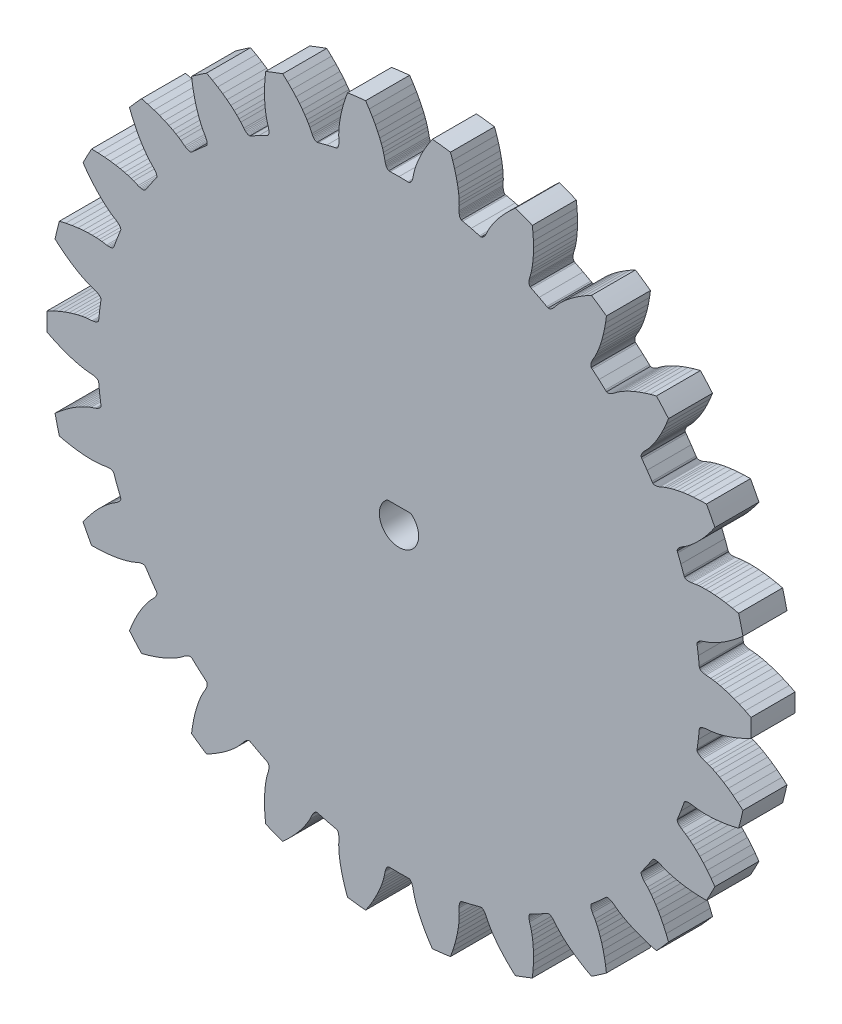
SolidWorks part; units mm, degrees
ref_plane "Front Plane" through (0, 0, 0) normal (0, 0, 1) x (1, 0, 0)
ref_plane "Top Plane" through (0, 0, 0) normal (0, 1, 0) x (1, 0, 0)
ref_plane "Right Plane" through (0, 0, 0) normal (1, 0, 0) x (0, 0, -1)
sketch "Model" plane through (0, 0, 0) normal (0, 0, 1) x (1, 0, 0)
  line L0 (53.9186, 11.3234) -> (53.1145, 10.6909)
  line L1 (53.1145, 10.6909) -> (52.3542, 10.1428)
  line L2 (52.3542, 10.1428) -> (51.6426, 9.6736)
  line L3 (51.6426, 9.6736) -> (50.9865, 9.2795)
  line L4 (50.9865, 9.2795) -> (50.3895, 8.954)
  line L5 (50.3895, 8.954) -> (49.8557, 8.6913)
  line L6 (49.8557, 8.6913) -> (49.3896, 8.4858)
  line L7 (49.3896, 8.4858) -> (48.9961, 8.3315)
  line L8 (48.9961, 8.3315) -> (48.275, 8.0914)
  line L9 (48.275, 8.0914) -> (48.0782, 8.0117)
  line L10 (48.0782, 8.0117) -> (47.9061, 7.9277)
  line L11 (47.9061, 7.9277) -> (47.7585, 7.8406)
  line L12 (47.7585, 7.8406) -> (47.6355, 7.7512)
  line L13 (47.6355, 7.7512) -> (47.5373, 7.6605)
  line L14 (47.5373, 7.6605) -> (47.4637, 7.5697)
  line L15 (47.4637, 7.5697) -> (47.4147, 7.4796)
  line L16 (47.4147, 7.4796) -> (47.3902, 7.3912)
  line L17 (47.3902, 7.3912) -> (47.3902, 7.3055)
  line L18 (47.3902, 7.3055) -> (47.4142, 7.1495)
  line L19 (47.4142, 7.1495) -> (47.6004, 5.7797)
  line L20 (47.6004, 5.7797) -> (47.7474, 4.4052)
  line L21 (47.7474, 4.4052) -> (47.7615, 4.248)
  line L22 (47.7615, 4.248) -> (47.782, 4.1648)
  line L23 (47.782, 4.1648) -> (47.8269, 4.0849)
  line L24 (47.8269, 4.0849) -> (47.896, 4.0091)
  line L25 (47.896, 4.0091) -> (47.9892, 3.9385)
  line L26 (47.9892, 3.9385) -> (48.1063, 3.874)
  line L27 (48.1063, 3.874) -> (48.2471, 3.8166)
  line L28 (48.2471, 3.8166) -> (48.4112, 3.7673)
  line L29 (48.4112, 3.7673) -> (48.5985, 3.727)
  line L30 (48.5985, 3.727) -> (48.8086, 3.6966)
  line L31 (48.8086, 3.6966) -> (49.5662, 3.6362)
  line L32 (49.5662, 3.6362) -> (49.9852, 3.5805)
  line L33 (49.9852, 3.5805) -> (50.4869, 3.4925)
  line L34 (50.4869, 3.4925) -> (51.0681, 3.3651)
  line L35 (51.0681, 3.3651) -> (51.7257, 3.192)
  line L36 (51.7257, 3.192) -> (52.457, 2.9663)
  line L37 (52.457, 2.9663) -> (53.2602, 2.6812)
  line L38 (53.2602, 2.6812) -> (54.1296, 2.3309)
  line L39 (54.1296, 2.3309) -> (55.0617, 1.9092)
  line L40 (55.0617, 1.9092) -> (55.9813, 1.447)
  line L41 (55.9813, -1.447) -> (55.0617, -1.9092)
  line L42 (55.0617, -1.9092) -> (54.1296, -2.3309)
  line L43 (54.1296, -2.3309) -> (53.2602, -2.6812)
  line L44 (53.2602, -2.6812) -> (52.457, -2.9663)
  line L45 (52.457, -2.9663) -> (51.7257, -3.192)
  line L46 (51.7257, -3.192) -> (51.0681, -3.3651)
  line L47 (51.0681, -3.3651) -> (50.4869, -3.4925)
  line L48 (50.4869, -3.4925) -> (49.9852, -3.5805)
  line L49 (49.9852, -3.5805) -> (49.5662, -3.6362)
  line L50 (49.5662, -3.6362) -> (48.8086, -3.6966)
  line L51 (48.8086, -3.6966) -> (48.5985, -3.727)
  line L52 (48.5985, -3.727) -> (48.4112, -3.7673)
  line L53 (48.4112, -3.7673) -> (48.2471, -3.8166)
  line L54 (48.2471, -3.8166) -> (48.1063, -3.874)
  line L55 (48.1063, -3.874) -> (47.9892, -3.9385)
  line L56 (47.9892, -3.9385) -> (47.896, -4.0091)
  line L57 (47.896, -4.0091) -> (47.8269, -4.0849)
  line L58 (47.8269, -4.0849) -> (47.782, -4.1648)
  line L59 (47.782, -4.1648) -> (47.7615, -4.248)
  line L60 (47.7615, -4.248) -> (47.7474, -4.4052)
  line L61 (47.7474, -4.4052) -> (47.6004, -5.7797)
  line L62 (47.6004, -5.7797) -> (47.4142, -7.1495)
  line L63 (47.4142, -7.1495) -> (47.3902, -7.3055)
  line L64 (47.3902, -7.3055) -> (47.3902, -7.3912)
  line L65 (47.3902, -7.3912) -> (47.4147, -7.4796)
  line L66 (47.4147, -7.4796) -> (47.4637, -7.5697)
  line L67 (47.4637, -7.5697) -> (47.5373, -7.6605)
  line L68 (47.5373, -7.6605) -> (47.6355, -7.7512)
  line L69 (47.6355, -7.7512) -> (47.7585, -7.8406)
  line L70 (47.7585, -7.8406) -> (47.9061, -7.9277)
  line L71 (47.9061, -7.9277) -> (48.0782, -8.0117)
  line L72 (48.0782, -8.0117) -> (48.275, -8.0914)
  line L73 (48.275, -8.0914) -> (48.9961, -8.3315)
  line L74 (48.9961, -8.3315) -> (49.3896, -8.4858)
  line L75 (49.3896, -8.4858) -> (49.8557, -8.6913)
  line L76 (49.8557, -8.6913) -> (50.3895, -8.954)
  line L77 (50.3895, -8.954) -> (50.9865, -9.2795)
  line L78 (50.9865, -9.2795) -> (51.6426, -9.6736)
  line L79 (51.6426, -9.6736) -> (52.3542, -10.1428)
  line L80 (52.3542, -10.1428) -> (53.1145, -10.6909)
  line L81 (53.1145, -10.6909) -> (53.9186, -11.3234)
  line L82 (53.9186, -11.3234) -> (54.7008, -11.9922)
  line L83 (54.0083, -14.8022) -> (53.0048, -15.0308)
  line L84 (53.0048, -15.0308) -> (51.9989, -15.2172)
  line L85 (51.9989, -15.2172) -> (51.0709, -15.3493)
  line L86 (51.0709, -15.3493) -> (50.2228, -15.4339)
  line L87 (50.2228, -15.4339) -> (49.4588, -15.478)
  line L88 (49.4588, -15.478) -> (48.7788, -15.4888)
  line L89 (48.7788, -15.4888) -> (48.1841, -15.4733)
  line L90 (48.1841, -15.4733) -> (47.6759, -15.4387)
  line L91 (47.6759, -15.4387) -> (47.2557, -15.3925)
  line L92 (47.2557, -15.3925) -> (46.5056, -15.2699)
  line L93 (46.5056, -15.2699) -> (46.2944, -15.2491)
  line L94 (46.2944, -15.2491) -> (46.1029, -15.2434)
  line L95 (46.1029, -15.2434) -> (45.9317, -15.252)
  line L96 (45.9317, -15.252) -> (45.7813, -15.274)
  line L97 (45.7813, -15.274) -> (45.6522, -15.3086)
  line L98 (45.6522, -15.3086) -> (45.5448, -15.3549)
  line L99 (45.5448, -15.3549) -> (45.4595, -15.4119)
  line L100 (45.4595, -15.4119) -> (45.3968, -15.4788)
  line L101 (45.3968, -15.4788) -> (45.357, -15.5546)
  line L102 (45.357, -15.5546) -> (45.3057, -15.7039)
  line L103 (45.3057, -15.7039) -> (44.834, -17.0033)
  line L104 (44.834, -17.0033) -> (44.3254, -18.2887)
  line L105 (44.3254, -18.2887) -> (44.2648, -18.4345)
  line L106 (44.2648, -18.4345) -> (44.2443, -18.5176)
  line L107 (44.2443, -18.5176) -> (44.2469, -18.6093)
  line L108 (44.2469, -18.6093) -> (44.2729, -18.7085)
  line L109 (44.2729, -18.7085) -> (44.3226, -18.8144)
  line L110 (44.3226, -18.8144) -> (44.3964, -18.9259)
  line L111 (44.3964, -18.9259) -> (44.4943, -19.0421)
  line L112 (44.4943, -19.0421) -> (44.6168, -19.162)
  line L113 (44.6168, -19.162) -> (44.7639, -19.2848)
  line L114 (44.7639, -19.2848) -> (44.9358, -19.4093)
  line L115 (44.9358, -19.4093) -> (45.5785, -19.8149)
  line L116 (45.5785, -19.8149) -> (45.9237, -20.0589)
  line L117 (45.9237, -20.0589) -> (46.327, -20.37)
  line L118 (46.327, -20.37) -> (46.7824, -20.7528)
  line L119 (46.7824, -20.7528) -> (47.2842, -21.2118)
  line L120 (47.2842, -21.2118) -> (47.8269, -21.7514)
  line L121 (47.8269, -21.7514) -> (48.4056, -22.3772)
  line L122 (48.4056, -22.3772) -> (49.0126, -23.0914)
  line L123 (49.0126, -23.0914) -> (49.6419, -23.8979)
  line L124 (49.6419, -23.8979) -> (50.2414, -24.7345)
  line L125 (48.8965, -27.2971) -> (47.8675, -27.2789)
  line L126 (47.8675, -27.2789) -> (46.8462, -27.2192)
  line L127 (46.8462, -27.2192) -> (45.9136, -27.1253)
  line L128 (45.9136, -27.1253) -> (45.0698, -27.0045)
  line L129 (45.0698, -27.0045) -> (44.3174, -26.8645)
  line L130 (44.3174, -26.8645) -> (43.6547, -26.7122)
  line L131 (43.6547, -26.7122) -> (43.0809, -26.5549)
  line L132 (43.0809, -26.5549) -> (42.5958, -26.3997)
  line L133 (42.5958, -26.3997) -> (42.1989, -26.2542)
  line L134 (42.1989, -26.2542) -> (41.4999, -25.9557)
  line L135 (41.4999, -25.9557) -> (41.2998, -25.8849)
  line L136 (41.2998, -25.8849) -> (41.1153, -25.8336)
  line L137 (41.1153, -25.8336) -> (40.947, -25.801)
  line L138 (40.947, -25.801) -> (40.7957, -25.7864)
  line L139 (40.7957, -25.7864) -> (40.662, -25.789)
  line L140 (40.662, -25.789) -> (40.5467, -25.8083)
  line L141 (40.5467, -25.8083) -> (40.4503, -25.8432)
  line L142 (40.4503, -25.8432) -> (40.3734, -25.8932)
  line L143 (40.3734, -25.8932) -> (40.3166, -25.9573)
  line L144 (40.3166, -25.9573) -> (40.231, -26.0899)
  line L145 (40.231, -26.0899) -> (39.4621, -27.2387)
  line L146 (39.4621, -27.2387) -> (38.6606, -28.3651)
  line L147 (38.6606, -28.3651) -> (38.5669, -28.4921)
  line L148 (38.5669, -28.4921) -> (38.5271, -28.5679)
  line L149 (38.5271, -28.5679) -> (38.5077, -28.6575)
  line L150 (38.5077, -28.6575) -> (38.5092, -28.7601)
  line L151 (38.5092, -28.7601) -> (38.5321, -28.8747)
  line L152 (38.5321, -28.8747) -> (38.577, -29.0007)
  line L153 (38.577, -29.0007) -> (38.6443, -29.1369)
  line L154 (38.6443, -29.1369) -> (38.7345, -29.2827)
  line L155 (38.7345, -29.2827) -> (38.848, -29.4371)
  line L156 (38.848, -29.4371) -> (38.9851, -29.5991)
  line L157 (38.9851, -29.5991) -> (39.5121, -30.1468)
  line L158 (39.5121, -30.1468) -> (39.7888, -30.4663)
  line L159 (39.7888, -30.4663) -> (40.1059, -30.8649)
  line L160 (40.1059, -30.8649) -> (40.4565, -31.3456)
  line L161 (40.4565, -31.3456) -> (40.8339, -31.9113)
  line L162 (40.8339, -31.9113) -> (41.2317, -32.5651)
  line L163 (41.2317, -32.5651) -> (41.6438, -33.3112)
  line L164 (41.6438, -33.3112) -> (42.0623, -34.1499)
  line L165 (42.0623, -34.1499) -> (42.4803, -35.0836)
  line L166 (42.4803, -35.0836) -> (42.8621, -36.0393)
  line L167 (40.943, -38.2055) -> (39.9482, -37.9417)
  line L168 (39.9482, -37.9417) -> (38.9709, -37.6393)
  line L169 (38.9709, -37.6393) -> (38.0879, -37.3249)
  line L170 (38.0879, -37.3249) -> (37.2976, -37.0058)
  line L171 (37.2976, -37.0058) -> (36.6006, -36.6897)
  line L172 (36.6006, -36.6897) -> (35.9935, -36.3833)
  line L173 (35.9935, -36.3833) -> (35.4741, -36.0932)
  line L174 (35.4741, -36.0932) -> (35.0402, -35.8264)
  line L175 (35.0402, -35.8264) -> (34.6896, -35.5902)
  line L176 (34.6896, -35.5902) -> (34.0824, -35.1331)
  line L177 (34.0824, -35.1331) -> (33.905, -35.0165)
  line L178 (33.905, -35.0165) -> (33.7381, -34.9224)
  line L179 (33.7381, -34.9224) -> (33.5826, -34.8505)
  line L180 (33.5826, -34.8505) -> (33.4392, -34.8001)
  line L181 (33.4392, -34.8001) -> (33.3087, -34.7707)
  line L182 (33.3087, -34.7707) -> (33.1922, -34.7618)
  line L183 (33.1922, -34.7618) -> (33.0902, -34.7727)
  line L184 (33.0902, -34.7727) -> (33.0035, -34.8027)
  line L185 (33.0035, -34.8027) -> (32.9331, -34.8514)
  line L186 (32.9331, -34.8514) -> (32.8183, -34.9597)
  line L187 (32.8183, -34.9597) -> (31.7967, -35.8911)
  line L188 (31.7967, -35.8911) -> (30.749, -36.7929)
  line L189 (30.749, -36.7929) -> (30.6276, -36.8938)
  line L190 (30.6276, -36.8938) -> (30.5708, -36.9579)
  line L191 (30.5708, -36.9579) -> (30.5305, -37.0403)
  line L192 (30.5305, -37.0403) -> (30.5074, -37.1402)
  line L193 (30.5074, -37.1402) -> (30.5023, -37.257)
  line L194 (30.5023, -37.257) -> (30.5157, -37.39)
  line L195 (30.5157, -37.39) -> (30.5485, -37.5385)
  line L196 (30.5485, -37.5385) -> (30.6011, -37.7016)
  line L197 (30.6011, -37.7016) -> (30.6744, -37.8786)
  line L198 (30.6744, -37.8786) -> (30.7687, -38.0687)
  line L199 (30.7687, -38.0687) -> (31.1493, -38.7266)
  line L200 (31.1493, -38.7266) -> (31.3416, -39.1031)
  line L201 (31.3416, -39.1031) -> (31.5541, -39.566)
  line L202 (31.5541, -39.566) -> (31.7795, -40.1166)
  line L203 (31.7795, -40.1166) -> (32.0105, -40.7562)
  line L204 (32.0105, -40.7562) -> (32.2402, -41.4862)
  line L205 (32.2402, -41.4862) -> (32.4618, -42.3092)
  line L206 (32.4618, -42.3092) -> (32.6674, -43.2237)
  line L207 (32.6674, -43.2237) -> (32.8498, -44.2303)
  line L208 (32.8498, -44.2303) -> (32.9918, -45.2497)
  line L209 (30.6101, -46.8937) -> (29.7074, -46.3994)
  line L210 (29.7074, -46.3994) -> (28.8309, -45.8719)
  line L211 (28.8309, -45.8719) -> (28.0487, -45.3554)
  line L212 (28.0487, -45.3554) -> (27.3577, -44.8563)
  line L213 (27.3577, -44.8563) -> (26.7566, -44.3827)
  line L214 (26.7566, -44.3827) -> (26.2405, -43.9399)
  line L215 (26.2405, -43.9399) -> (25.8056, -43.5339)
  line L216 (25.8056, -43.5339) -> (25.4481, -43.171)
  line L217 (25.4481, -43.171) -> (25.1643, -42.8578)
  line L218 (25.1643, -42.8578) -> (24.6842, -42.2686)
  line L219 (24.6842, -42.2686) -> (24.5398, -42.113)
  line L220 (24.5398, -42.113) -> (24.4003, -41.9817)
  line L221 (24.4003, -41.9817) -> (24.2664, -41.8746)
  line L222 (24.2664, -41.8746) -> (24.1393, -41.7914)
  line L223 (24.1393, -41.7914) -> (24.0197, -41.7317)
  line L224 (24.0197, -41.7317) -> (23.9086, -41.6951)
  line L225 (23.9086, -41.6951) -> (23.807, -41.6812)
  line L226 (23.807, -41.6812) -> (23.7157, -41.6897)
  line L227 (23.7157, -41.6897) -> (23.6356, -41.72)
  line L228 (23.6356, -41.72) -> (23.4982, -41.7978)
  line L229 (23.4982, -41.7978) -> (22.2835, -42.4576)
  line L230 (22.2835, -42.4576) -> (21.0504, -43.0825)
  line L231 (21.0504, -43.0825) -> (20.9084, -43.1514)
  line L232 (20.9084, -43.1514) -> (20.8379, -43.2001)
  line L233 (20.8379, -43.2001) -> (20.7791, -43.2704)
  line L234 (20.7791, -43.2704) -> (20.7327, -43.3619)
  line L235 (20.7327, -43.3619) -> (20.6997, -43.4741)
  line L236 (20.6997, -43.4741) -> (20.681, -43.6064)
  line L237 (20.681, -43.6064) -> (20.6772, -43.7584)
  line L238 (20.6772, -43.7584) -> (20.6893, -43.9294)
  line L239 (20.6893, -43.9294) -> (20.7181, -44.1188)
  line L240 (20.7181, -44.1188) -> (20.7642, -44.326)
  line L241 (20.7642, -44.326) -> (20.9763, -45.0558)
  line L242 (20.9763, -45.0558) -> (21.0729, -45.4673)
  line L243 (21.0729, -45.4673) -> (21.1684, -45.9677)
  line L244 (21.1684, -45.9677) -> (21.2555, -46.5562)
  line L245 (21.2555, -46.5562) -> (21.3267, -47.2325)
  line L246 (21.3267, -47.2325) -> (21.3751, -47.9962)
  line L247 (21.3751, -47.9962) -> (21.3933, -48.8484)
  line L248 (21.3933, -48.8484) -> (21.374, -49.7855)
  line L249 (21.374, -49.7855) -> (21.3103, -50.8066)
  line L250 (21.3103, -50.8066) -> (21.2042, -51.8303)
  line L251 (18.4982, -52.8565) -> (17.74, -52.1606)
  line L252 (17.74, -52.1606) -> (17.0152, -51.4386)
  line L253 (17.0152, -51.4386) -> (16.3794, -50.7499)
  line L254 (16.3794, -50.7499) -> (15.8279, -50.1)
  line L255 (15.8279, -50.1) -> (15.3576, -49.4963)
  line L256 (15.3576, -49.4963) -> (14.9625, -48.9428)
  line L257 (14.9625, -48.9428) -> (14.6374, -48.4445)
  line L258 (14.6374, -48.4445) -> (14.3772, -48.0067)
  line L259 (14.3772, -48.0067) -> (14.1765, -47.6346)
  line L260 (14.1765, -47.6346) -> (13.8513, -46.9477)
  line L261 (13.8513, -46.9477) -> (13.7485, -46.762)
  line L262 (13.7485, -46.762) -> (13.6444, -46.6012)
  line L263 (13.6444, -46.6012) -> (13.54, -46.4652)
  line L264 (13.54, -46.4652) -> (13.4365, -46.3539)
  line L265 (13.4365, -46.3539) -> (13.3347, -46.2673)
  line L266 (13.3347, -46.2673) -> (13.2356, -46.2052)
  line L267 (13.2356, -46.2052) -> (13.1402, -46.1674)
  line L268 (13.1402, -46.1674) -> (13.0496, -46.1538)
  line L269 (13.0496, -46.1538) -> (12.9645, -46.1641)
  line L270 (12.9645, -46.1641) -> (12.8126, -46.2067)
  line L271 (12.8126, -46.2067) -> (11.4752, -46.5567)
  line L272 (11.4752, -46.5567) -> (10.1284, -46.8683)
  line L273 (10.1284, -46.8683) -> (9.974, -46.9012)
  line L274 (9.974, -46.9012) -> (9.8939, -46.9316)
  line L275 (9.8939, -46.9316) -> (9.82, -46.9858)
  line L276 (9.82, -46.9858) -> (9.7531, -47.0635)
  line L277 (9.7531, -47.0635) -> (9.6942, -47.1646)
  line L278 (9.6942, -47.1646) -> (9.6443, -47.2886)
  line L279 (9.6443, -47.2886) -> (9.6043, -47.4353)
  line L280 (9.6043, -47.4353) -> (9.5752, -47.6042)
  line L281 (9.5752, -47.6042) -> (9.5577, -47.7949)
  line L282 (9.5577, -47.7949) -> (9.5529, -48.0071)
  line L283 (9.5529, -48.0071) -> (9.5842, -48.7665)
  line L284 (9.5842, -48.7665) -> (9.5795, -49.1892)
  line L285 (9.5795, -49.1892) -> (9.5525, -49.6979)
  line L286 (9.5525, -49.6979) -> (9.4962, -50.2901)
  line L287 (9.4962, -50.2901) -> (9.4036, -50.9638)
  line L288 (9.4036, -50.9638) -> (9.2677, -51.717)
  line L289 (9.2677, -51.717) -> (9.0814, -52.5487)
  line L290 (9.0814, -52.5487) -> (8.8385, -53.454)
  line L291 (8.8385, -53.454) -> (8.5322, -54.4301)
  line L292 (8.5322, -54.4301) -> (8.1843, -55.3987)
  line L293 (5.3113, -55.7475) -> (4.7417, -54.8903)
  line L294 (4.7417, -54.8903) -> (4.2107, -54.0159)
  line L295 (4.2107, -54.0159) -> (3.7582, -53.1951)
  line L296 (3.7582, -53.1951) -> (3.3783, -52.4321)
  line L297 (3.3783, -52.4321) -> (3.0661, -51.7333)
  line L298 (3.0661, -51.7333) -> (2.815, -51.1014)
  line L299 (2.815, -51.1014) -> (2.6185, -50.5398)
  line L300 (2.6185, -50.5398) -> (2.4706, -50.0524)
  line L301 (2.4706, -50.0524) -> (2.3649, -49.6431)
  line L302 (2.3649, -49.6431) -> (2.2135, -48.8983)
  line L303 (2.2135, -48.8983) -> (2.1581, -48.6934)
  line L304 (2.1581, -48.6934) -> (2.0955, -48.5123)
  line L305 (2.0955, -48.5123) -> (2.0267, -48.3553)
  line L306 (2.0267, -48.3553) -> (1.9528, -48.2225)
  line L307 (1.9528, -48.2225) -> (1.8747, -48.114)
  line L308 (1.8747, -48.114) -> (1.7934, -48.03)
  line L309 (1.7934, -48.03) -> (1.7098, -47.9705)
  line L310 (1.7098, -47.9705) -> (1.625, -47.9356)
  line L311 (1.625, -47.9356) -> (1.54, -47.9253)
  line L312 (1.54, -47.9253) -> (1.3823, -47.9302)
  line L313 (1.3823, -47.9302) -> (0, -47.95)
  line L314 (0, -47.95) -> (-1.3823, -47.9302)
  line L315 (-1.3823, -47.9302) -> (-1.54, -47.9253)
  line L316 (-1.54, -47.9253) -> (-1.625, -47.9356)
  line L317 (-1.625, -47.9356) -> (-1.7098, -47.9705)
  line L318 (-1.7098, -47.9705) -> (-1.7934, -48.03)
  line L319 (-1.7934, -48.03) -> (-1.8747, -48.114)
  line L320 (-1.8747, -48.114) -> (-1.9528, -48.2225)
  line L321 (-1.9528, -48.2225) -> (-2.0267, -48.3553)
  line L322 (-2.0267, -48.3553) -> (-2.0955, -48.5123)
  line L323 (-2.0955, -48.5123) -> (-2.1581, -48.6934)
  line L324 (-2.1581, -48.6934) -> (-2.2135, -48.8983)
  line L325 (-2.2135, -48.8983) -> (-2.3649, -49.6431)
  line L326 (-2.3649, -49.6431) -> (-2.4706, -50.0524)
  line L327 (-2.4706, -50.0524) -> (-2.6185, -50.5398)
  line L328 (-2.6185, -50.5398) -> (-2.815, -51.1014)
  line L329 (-2.815, -51.1014) -> (-3.0661, -51.7333)
  line L330 (-3.0661, -51.7333) -> (-3.3783, -52.4321)
  line L331 (-3.3783, -52.4321) -> (-3.7582, -53.1951)
  line L332 (-3.7582, -53.1951) -> (-4.2107, -54.0159)
  line L333 (-4.2107, -54.0159) -> (-4.7417, -54.8903)
  line L334 (-4.7417, -54.8903) -> (-5.3113, -55.7475)
  line L335 (-8.1843, -55.3987) -> (-8.5322, -54.4301)
  line L336 (-8.5322, -54.4301) -> (-8.8385, -53.454)
  line L337 (-8.8385, -53.454) -> (-9.0814, -52.5487)
  line L338 (-9.0814, -52.5487) -> (-9.2677, -51.717)
  line L339 (-9.2677, -51.717) -> (-9.4036, -50.9638)
  line L340 (-9.4036, -50.9638) -> (-9.4962, -50.2901)
  line L341 (-9.4962, -50.2901) -> (-9.5525, -49.6979)
  line L342 (-9.5525, -49.6979) -> (-9.5795, -49.1892)
  line L343 (-9.5795, -49.1892) -> (-9.5842, -48.7665)
  line L344 (-9.5842, -48.7665) -> (-9.5529, -48.0071)
  line L345 (-9.5529, -48.0071) -> (-9.5577, -47.7949)
  line L346 (-9.5577, -47.7949) -> (-9.5752, -47.6042)
  line L347 (-9.5752, -47.6042) -> (-9.6043, -47.4353)
  line L348 (-9.6043, -47.4353) -> (-9.6443, -47.2886)
  line L349 (-9.6443, -47.2886) -> (-9.6942, -47.1646)
  line L350 (-9.6942, -47.1646) -> (-9.7531, -47.0635)
  line L351 (-9.7531, -47.0635) -> (-9.82, -46.9858)
  line L352 (-9.82, -46.9858) -> (-9.8939, -46.9316)
  line L353 (-9.8939, -46.9316) -> (-9.974, -46.9012)
  line L354 (-9.974, -46.9012) -> (-10.1284, -46.8683)
  line L355 (-10.1284, -46.8683) -> (-11.4752, -46.5567)
  line L356 (-11.4752, -46.5567) -> (-12.8126, -46.2067)
  line L357 (-12.8126, -46.2067) -> (-12.9645, -46.1641)
  line L358 (-12.9645, -46.1641) -> (-13.0496, -46.1538)
  line L359 (-13.0496, -46.1538) -> (-13.1402, -46.1674)
  line L360 (-13.1402, -46.1674) -> (-13.2356, -46.2052)
  line L361 (-13.2356, -46.2052) -> (-13.3347, -46.2673)
  line L362 (-13.3347, -46.2673) -> (-13.4365, -46.3539)
  line L363 (-13.4365, -46.3539) -> (-13.54, -46.4652)
  line L364 (-13.54, -46.4652) -> (-13.6444, -46.6012)
  line L365 (-13.6444, -46.6012) -> (-13.7485, -46.762)
  line L366 (-13.7485, -46.762) -> (-13.8513, -46.9477)
  line L367 (-13.8513, -46.9477) -> (-14.1765, -47.6346)
  line L368 (-14.1765, -47.6346) -> (-14.3772, -48.0067)
  line L369 (-14.3772, -48.0067) -> (-14.6374, -48.4445)
  line L370 (-14.6374, -48.4445) -> (-14.9625, -48.9428)
  line L371 (-14.9625, -48.9428) -> (-15.3576, -49.4963)
  line L372 (-15.3576, -49.4963) -> (-15.8279, -50.1)
  line L373 (-15.8279, -50.1) -> (-16.3794, -50.7499)
  line L374 (-16.3794, -50.7499) -> (-17.0152, -51.4386)
  line L375 (-17.0152, -51.4386) -> (-17.74, -52.1606)
  line L376 (-17.74, -52.1606) -> (-18.4982, -52.8565)
  line L377 (-21.2042, -51.8303) -> (-21.3103, -50.8066)
  line L378 (-21.3103, -50.8066) -> (-21.374, -49.7855)
  line L379 (-21.374, -49.7855) -> (-21.3933, -48.8484)
  line L380 (-21.3933, -48.8484) -> (-21.3751, -47.9962)
  line L381 (-21.3751, -47.9962) -> (-21.3267, -47.2325)
  line L382 (-21.3267, -47.2325) -> (-21.2555, -46.5562)
  line L383 (-21.2555, -46.5562) -> (-21.1684, -45.9677)
  line L384 (-21.1684, -45.9677) -> (-21.0729, -45.4673)
  line L385 (-21.0729, -45.4673) -> (-20.9763, -45.0558)
  line L386 (-20.9763, -45.0558) -> (-20.7642, -44.326)
  line L387 (-20.7642, -44.326) -> (-20.7181, -44.1188)
  line L388 (-20.7181, -44.1188) -> (-20.6893, -43.9294)
  line L389 (-20.6893, -43.9294) -> (-20.6772, -43.7584)
  line L390 (-20.6772, -43.7584) -> (-20.681, -43.6064)
  line L391 (-20.681, -43.6064) -> (-20.6997, -43.4741)
  line L392 (-20.6997, -43.4741) -> (-20.7327, -43.3619)
  line L393 (-20.7327, -43.3619) -> (-20.7791, -43.2704)
  line L394 (-20.7791, -43.2704) -> (-20.8379, -43.2001)
  line L395 (-20.8379, -43.2001) -> (-20.9084, -43.1514)
  line L396 (-20.9084, -43.1514) -> (-21.0504, -43.0825)
  line L397 (-21.0504, -43.0825) -> (-22.2835, -42.4576)
  line L398 (-22.2835, -42.4576) -> (-23.4982, -41.7978)
  line L399 (-23.4982, -41.7978) -> (-23.6356, -41.72)
  line L400 (-23.6356, -41.72) -> (-23.7157, -41.6897)
  line L401 (-23.7157, -41.6897) -> (-23.807, -41.6812)
  line L402 (-23.807, -41.6812) -> (-23.9086, -41.6951)
  line L403 (-23.9086, -41.6951) -> (-24.0197, -41.7317)
  line L404 (-24.0197, -41.7317) -> (-24.1393, -41.7914)
  line L405 (-24.1393, -41.7914) -> (-24.2664, -41.8746)
  line L406 (-24.2664, -41.8746) -> (-24.4003, -41.9817)
  line L407 (-24.4003, -41.9817) -> (-24.5398, -42.113)
  line L408 (-24.5398, -42.113) -> (-24.6842, -42.2686)
  line L409 (-24.6842, -42.2686) -> (-25.1643, -42.8578)
  line L410 (-25.1643, -42.8578) -> (-25.4481, -43.171)
  line L411 (-25.4481, -43.171) -> (-25.8056, -43.5339)
  line L412 (-25.8056, -43.5339) -> (-26.2405, -43.9399)
  line L413 (-26.2405, -43.9399) -> (-26.7566, -44.3827)
  line L414 (-26.7566, -44.3827) -> (-27.3577, -44.8563)
  line L415 (-27.3577, -44.8563) -> (-28.0487, -45.3554)
  line L416 (-28.0487, -45.3554) -> (-28.8309, -45.8719)
  line L417 (-28.8309, -45.8719) -> (-29.7074, -46.3994)
  line L418 (-29.7074, -46.3994) -> (-30.6101, -46.8937)
  line L419 (-32.9918, -45.2497) -> (-32.8498, -44.2303)
  line L420 (-32.8498, -44.2303) -> (-32.6674, -43.2237)
  line L421 (-32.6674, -43.2237) -> (-32.4618, -42.3092)
  line L422 (-32.4618, -42.3092) -> (-32.2402, -41.4862)
  line L423 (-32.2402, -41.4862) -> (-32.0105, -40.7562)
  line L424 (-32.0105, -40.7562) -> (-31.7795, -40.1166)
  line L425 (-31.7795, -40.1166) -> (-31.5541, -39.566)
  line L426 (-31.5541, -39.566) -> (-31.3416, -39.1031)
  line L427 (-31.3416, -39.1031) -> (-31.1493, -38.7266)
  line L428 (-31.1493, -38.7266) -> (-30.7687, -38.0687)
  line L429 (-30.7687, -38.0687) -> (-30.6744, -37.8786)
  line L430 (-30.6744, -37.8786) -> (-30.6011, -37.7016)
  line L431 (-30.6011, -37.7016) -> (-30.5485, -37.5385)
  line L432 (-30.5485, -37.5385) -> (-30.5157, -37.39)
  line L433 (-30.5157, -37.39) -> (-30.5023, -37.257)
  line L434 (-30.5023, -37.257) -> (-30.5074, -37.1402)
  line L435 (-30.5074, -37.1402) -> (-30.5305, -37.0403)
  line L436 (-30.5305, -37.0403) -> (-30.5708, -36.9579)
  line L437 (-30.5708, -36.9579) -> (-30.6276, -36.8938)
  line L438 (-30.6276, -36.8938) -> (-30.749, -36.7929)
  line L439 (-30.749, -36.7929) -> (-31.7967, -35.8911)
  line L440 (-31.7967, -35.8911) -> (-32.8183, -34.9597)
  line L441 (-32.8183, -34.9597) -> (-32.9331, -34.8514)
  line L442 (-32.9331, -34.8514) -> (-33.0035, -34.8027)
  line L443 (-33.0035, -34.8027) -> (-33.0902, -34.7727)
  line L444 (-33.0902, -34.7727) -> (-33.1922, -34.7618)
  line L445 (-33.1922, -34.7618) -> (-33.3087, -34.7707)
  line L446 (-33.3087, -34.7707) -> (-33.4392, -34.8001)
  line L447 (-33.4392, -34.8001) -> (-33.5826, -34.8505)
  line L448 (-33.5826, -34.8505) -> (-33.7381, -34.9224)
  line L449 (-33.7381, -34.9224) -> (-33.905, -35.0165)
  line L450 (-33.905, -35.0165) -> (-34.0824, -35.1331)
  line L451 (-34.0824, -35.1331) -> (-34.6896, -35.5902)
  line L452 (-34.6896, -35.5902) -> (-35.0402, -35.8264)
  line L453 (-35.0402, -35.8264) -> (-35.4741, -36.0932)
  line L454 (-35.4741, -36.0932) -> (-35.9935, -36.3833)
  line L455 (-35.9935, -36.3833) -> (-36.6006, -36.6897)
  line L456 (-36.6006, -36.6897) -> (-37.2976, -37.0058)
  line L457 (-37.2976, -37.0058) -> (-38.0879, -37.3249)
  line L458 (-38.0879, -37.3249) -> (-38.9709, -37.6393)
  line L459 (-38.9709, -37.6393) -> (-39.9482, -37.9417)
  line L460 (-39.9482, -37.9417) -> (-40.943, -38.2055)
  line L461 (-42.8621, -36.0393) -> (-42.4803, -35.0836)
  line L462 (-42.4803, -35.0836) -> (-42.0623, -34.1499)
  line L463 (-42.0623, -34.1499) -> (-41.6438, -33.3112)
  line L464 (-41.6438, -33.3112) -> (-41.2317, -32.5651)
  line L465 (-41.2317, -32.5651) -> (-40.8339, -31.9113)
  line L466 (-40.8339, -31.9113) -> (-40.4565, -31.3456)
  line L467 (-40.4565, -31.3456) -> (-40.1059, -30.8649)
  line L468 (-40.1059, -30.8649) -> (-39.7888, -30.4663)
  line L469 (-39.7888, -30.4663) -> (-39.5121, -30.1468)
  line L470 (-39.5121, -30.1468) -> (-38.9851, -29.5991)
  line L471 (-38.9851, -29.5991) -> (-38.848, -29.4371)
  line L472 (-38.848, -29.4371) -> (-38.7345, -29.2827)
  line L473 (-38.7345, -29.2827) -> (-38.6443, -29.1369)
  line L474 (-38.6443, -29.1369) -> (-38.577, -29.0007)
  line L475 (-38.577, -29.0007) -> (-38.5321, -28.8747)
  line L476 (-38.5321, -28.8747) -> (-38.5092, -28.7601)
  line L477 (-38.5092, -28.7601) -> (-38.5077, -28.6575)
  line L478 (-38.5077, -28.6575) -> (-38.5271, -28.5679)
  line L479 (-38.5271, -28.5679) -> (-38.5669, -28.4921)
  line L480 (-38.5669, -28.4921) -> (-38.6606, -28.3651)
  line L481 (-38.6606, -28.3651) -> (-39.4621, -27.2387)
  line L482 (-39.4621, -27.2387) -> (-40.231, -26.0899)
  line L483 (-40.231, -26.0899) -> (-40.3166, -25.9573)
  line L484 (-40.3166, -25.9573) -> (-40.3734, -25.8932)
  line L485 (-40.3734, -25.8932) -> (-40.4503, -25.8432)
  line L486 (-40.4503, -25.8432) -> (-40.5467, -25.8083)
  line L487 (-40.5467, -25.8083) -> (-40.662, -25.789)
  line L488 (-40.662, -25.789) -> (-40.7957, -25.7864)
  line L489 (-40.7957, -25.7864) -> (-40.947, -25.801)
  line L490 (-40.947, -25.801) -> (-41.1153, -25.8336)
  line L491 (-41.1153, -25.8336) -> (-41.2998, -25.8849)
  line L492 (-41.2998, -25.8849) -> (-41.4999, -25.9557)
  line L493 (-41.4999, -25.9557) -> (-42.1989, -26.2542)
  line L494 (-42.1989, -26.2542) -> (-42.5958, -26.3997)
  line L495 (-42.5958, -26.3997) -> (-43.0809, -26.5549)
  line L496 (-43.0809, -26.5549) -> (-43.6547, -26.7122)
  line L497 (-43.6547, -26.7122) -> (-44.3174, -26.8645)
  line L498 (-44.3174, -26.8645) -> (-45.0698, -27.0045)
  line L499 (-45.0698, -27.0045) -> (-45.9136, -27.1253)
  line L500 (-45.9136, -27.1253) -> (-46.8462, -27.2192)
  line L501 (-46.8462, -27.2192) -> (-47.8675, -27.2789)
  line L502 (-47.8675, -27.2789) -> (-48.8965, -27.2971)
  line L503 (-50.2414, -24.7345) -> (-49.6419, -23.8979)
  line L504 (-49.6419, -23.8979) -> (-49.0126, -23.0914)
  line L505 (-49.0126, -23.0914) -> (-48.4056, -22.3772)
  line L506 (-48.4056, -22.3772) -> (-47.8269, -21.7514)
  line L507 (-47.8269, -21.7514) -> (-47.2842, -21.2118)
  line L508 (-47.2842, -21.2118) -> (-46.7824, -20.7528)
  line L509 (-46.7824, -20.7528) -> (-46.327, -20.37)
  line L510 (-46.327, -20.37) -> (-45.9237, -20.0589)
  line L511 (-45.9237, -20.0589) -> (-45.5785, -19.8149)
  line L512 (-45.5785, -19.8149) -> (-44.9358, -19.4093)
  line L513 (-44.9358, -19.4093) -> (-44.7639, -19.2848)
  line L514 (-44.7639, -19.2848) -> (-44.6168, -19.162)
  line L515 (-44.6168, -19.162) -> (-44.4943, -19.0421)
  line L516 (-44.4943, -19.0421) -> (-44.3964, -18.9259)
  line L517 (-44.3964, -18.9259) -> (-44.3226, -18.8144)
  line L518 (-44.3226, -18.8144) -> (-44.2729, -18.7085)
  line L519 (-44.2729, -18.7085) -> (-44.2469, -18.6093)
  line L520 (-44.2469, -18.6093) -> (-44.2443, -18.5176)
  line L521 (-44.2443, -18.5176) -> (-44.2648, -18.4345)
  line L522 (-44.2648, -18.4345) -> (-44.3254, -18.2887)
  line L523 (-44.3254, -18.2887) -> (-44.834, -17.0033)
  line L524 (-44.834, -17.0033) -> (-45.3057, -15.7039)
  line L525 (-45.3057, -15.7039) -> (-45.357, -15.5546)
  line L526 (-45.357, -15.5546) -> (-45.3968, -15.4788)
  line L527 (-45.3968, -15.4788) -> (-45.4595, -15.4119)
  line L528 (-45.4595, -15.4119) -> (-45.5448, -15.3549)
  line L529 (-45.5448, -15.3549) -> (-45.6522, -15.3086)
  line L530 (-45.6522, -15.3086) -> (-45.7813, -15.274)
  line L531 (-45.7813, -15.274) -> (-45.9317, -15.252)
  line L532 (-45.9317, -15.252) -> (-46.1029, -15.2434)
  line L533 (-46.1029, -15.2434) -> (-46.2944, -15.2491)
  line L534 (-46.2944, -15.2491) -> (-46.5056, -15.2699)
  line L535 (-46.5056, -15.2699) -> (-47.2557, -15.3925)
  line L536 (-47.2557, -15.3925) -> (-47.6759, -15.4387)
  line L537 (-47.6759, -15.4387) -> (-48.1841, -15.4733)
  line L538 (-48.1841, -15.4733) -> (-48.7788, -15.4888)
  line L539 (-48.7788, -15.4888) -> (-49.4588, -15.478)
  line L540 (-49.4588, -15.478) -> (-50.2228, -15.4339)
  line L541 (-50.2228, -15.4339) -> (-51.0709, -15.3493)
  line L542 (-51.0709, -15.3493) -> (-51.9989, -15.2172)
  line L543 (-51.9989, -15.2172) -> (-53.0048, -15.0308)
  line L544 (-53.0048, -15.0308) -> (-54.0083, -14.8022)
  line L545 (-54.7008, -11.9922) -> (-53.9186, -11.3234)
  line L546 (-53.9186, -11.3234) -> (-53.1145, -10.6909)
  line L547 (-53.1145, -10.6909) -> (-52.3542, -10.1428)
  line L548 (-52.3542, -10.1428) -> (-51.6426, -9.6736)
  line L549 (-51.6426, -9.6736) -> (-50.9865, -9.2795)
  line L550 (-50.9865, -9.2795) -> (-50.3895, -8.954)
  line L551 (-50.3895, -8.954) -> (-49.8557, -8.6913)
  line L552 (-49.8557, -8.6913) -> (-49.3896, -8.4858)
  line L553 (-49.3896, -8.4858) -> (-48.9961, -8.3315)
  line L554 (-48.9961, -8.3315) -> (-48.275, -8.0914)
  line L555 (-48.275, -8.0914) -> (-48.0782, -8.0117)
  line L556 (-48.0782, -8.0117) -> (-47.9061, -7.9277)
  line L557 (-47.9061, -7.9277) -> (-47.7585, -7.8406)
  line L558 (-47.7585, -7.8406) -> (-47.6355, -7.7512)
  line L559 (-47.6355, -7.7512) -> (-47.5373, -7.6605)
  line L560 (-47.5373, -7.6605) -> (-47.4637, -7.5697)
  line L561 (-47.4637, -7.5697) -> (-47.4147, -7.4796)
  line L562 (-47.4147, -7.4796) -> (-47.3902, -7.3912)
  line L563 (-47.3902, -7.3912) -> (-47.3902, -7.3055)
  line L564 (-47.3902, -7.3055) -> (-47.4142, -7.1495)
  line L565 (-47.4142, -7.1495) -> (-47.6004, -5.7797)
  line L566 (-47.6004, -5.7797) -> (-47.7474, -4.4052)
  line L567 (-47.7474, -4.4052) -> (-47.7615, -4.248)
  line L568 (-47.7615, -4.248) -> (-47.782, -4.1648)
  line L569 (-47.782, -4.1648) -> (-47.8269, -4.0849)
  line L570 (-47.8269, -4.0849) -> (-47.896, -4.0091)
  line L571 (-47.896, -4.0091) -> (-47.9892, -3.9385)
  line L572 (-47.9892, -3.9385) -> (-48.1063, -3.874)
  line L573 (-48.1063, -3.874) -> (-48.2471, -3.8166)
  line L574 (-48.2471, -3.8166) -> (-48.4112, -3.7673)
  line L575 (-48.4112, -3.7673) -> (-48.5985, -3.727)
  line L576 (-48.5985, -3.727) -> (-48.8086, -3.6966)
  line L577 (-48.8086, -3.6966) -> (-49.5662, -3.6362)
  line L578 (-49.5662, -3.6362) -> (-49.9852, -3.5805)
  line L579 (-49.9852, -3.5805) -> (-50.4869, -3.4925)
  line L580 (-50.4869, -3.4925) -> (-51.0681, -3.3651)
  line L581 (-51.0681, -3.3651) -> (-51.7257, -3.192)
  line L582 (-51.7257, -3.192) -> (-52.457, -2.9663)
  line L583 (-52.457, -2.9663) -> (-53.2602, -2.6812)
  line L584 (-53.2602, -2.6812) -> (-54.1296, -2.3309)
  line L585 (-54.1296, -2.3309) -> (-55.0617, -1.9092)
  line L586 (-55.0617, -1.9092) -> (-55.9813, -1.447)
  line L587 (-55.9813, 1.447) -> (-55.0617, 1.9092)
  line L588 (-55.0617, 1.9092) -> (-54.1296, 2.3309)
  line L589 (-54.1296, 2.3309) -> (-53.2602, 2.6812)
  line L590 (-53.2602, 2.6812) -> (-52.457, 2.9663)
  line L591 (-52.457, 2.9663) -> (-51.7257, 3.192)
  line L592 (-51.7257, 3.192) -> (-51.0681, 3.3651)
  line L593 (-51.0681, 3.3651) -> (-50.4869, 3.4925)
  line L594 (-50.4869, 3.4925) -> (-49.9852, 3.5805)
  line L595 (-49.9852, 3.5805) -> (-49.5662, 3.6362)
  line L596 (-49.5662, 3.6362) -> (-48.8086, 3.6966)
  line L597 (-48.8086, 3.6966) -> (-48.5985, 3.727)
  line L598 (-48.5985, 3.727) -> (-48.4112, 3.7673)
  line L599 (-48.4112, 3.7673) -> (-48.2471, 3.8166)
  line L600 (-48.2471, 3.8166) -> (-48.1063, 3.874)
  line L601 (-48.1063, 3.874) -> (-47.9892, 3.9385)
  line L602 (-47.9892, 3.9385) -> (-47.896, 4.0091)
  line L603 (-47.896, 4.0091) -> (-47.8269, 4.0849)
  line L604 (-47.8269, 4.0849) -> (-47.782, 4.1648)
  line L605 (-47.782, 4.1648) -> (-47.7615, 4.248)
  line L606 (-47.7615, 4.248) -> (-47.7474, 4.4052)
  line L607 (-47.7474, 4.4052) -> (-47.6004, 5.7797)
  line L608 (-47.6004, 5.7797) -> (-47.4142, 7.1495)
  line L609 (-47.4142, 7.1495) -> (-47.3902, 7.3055)
  line L610 (-47.3902, 7.3055) -> (-47.3902, 7.3912)
  line L611 (-47.3902, 7.3912) -> (-47.4147, 7.4796)
  line L612 (-47.4147, 7.4796) -> (-47.4637, 7.5697)
  line L613 (-47.4637, 7.5697) -> (-47.5373, 7.6605)
  line L614 (-47.5373, 7.6605) -> (-47.6355, 7.7512)
  line L615 (-47.6355, 7.7512) -> (-47.7585, 7.8406)
  line L616 (-47.7585, 7.8406) -> (-47.9061, 7.9277)
  line L617 (-47.9061, 7.9277) -> (-48.0782, 8.0117)
  line L618 (-48.0782, 8.0117) -> (-48.275, 8.0914)
  line L619 (-48.275, 8.0914) -> (-48.9961, 8.3315)
  line L620 (-48.9961, 8.3315) -> (-49.3896, 8.4858)
  line L621 (-49.3896, 8.4858) -> (-49.8557, 8.6913)
  line L622 (-49.8557, 8.6913) -> (-50.3895, 8.954)
  line L623 (-50.3895, 8.954) -> (-50.9865, 9.2795)
  line L624 (-50.9865, 9.2795) -> (-51.6426, 9.6736)
  line L625 (-51.6426, 9.6736) -> (-52.3542, 10.1428)
  line L626 (-52.3542, 10.1428) -> (-53.1145, 10.6909)
  line L627 (-53.1145, 10.6909) -> (-53.9186, 11.3234)
  line L628 (-53.9186, 11.3234) -> (-54.7008, 11.9922)
  line L629 (-54.0083, 14.8022) -> (-53.0048, 15.0308)
  line L630 (-53.0048, 15.0308) -> (-51.9989, 15.2172)
  line L631 (-51.9989, 15.2172) -> (-51.0709, 15.3493)
  line L632 (-51.0709, 15.3493) -> (-50.2228, 15.4339)
  line L633 (-50.2228, 15.4339) -> (-49.4588, 15.478)
  line L634 (-49.4588, 15.478) -> (-48.7788, 15.4888)
  line L635 (-48.7788, 15.4888) -> (-48.1841, 15.4733)
  line L636 (-48.1841, 15.4733) -> (-47.6759, 15.4387)
  line L637 (-47.6759, 15.4387) -> (-47.2557, 15.3925)
  line L638 (-47.2557, 15.3925) -> (-46.5056, 15.2699)
  line L639 (-46.5056, 15.2699) -> (-46.2944, 15.2491)
  line L640 (-46.2944, 15.2491) -> (-46.1029, 15.2434)
  line L641 (-46.1029, 15.2434) -> (-45.9317, 15.252)
  line L642 (-45.9317, 15.252) -> (-45.7813, 15.274)
  line L643 (-45.7813, 15.274) -> (-45.6522, 15.3086)
  line L644 (-45.6522, 15.3086) -> (-45.5448, 15.3549)
  line L645 (-45.5448, 15.3549) -> (-45.4595, 15.4119)
  line L646 (-45.4595, 15.4119) -> (-45.3968, 15.4788)
  line L647 (-45.3968, 15.4788) -> (-45.357, 15.5546)
  line L648 (-45.357, 15.5546) -> (-45.3057, 15.7039)
  line L649 (-45.3057, 15.7039) -> (-44.834, 17.0033)
  line L650 (-44.834, 17.0033) -> (-44.3254, 18.2887)
  line L651 (-44.3254, 18.2887) -> (-44.2648, 18.4345)
  line L652 (-44.2648, 18.4345) -> (-44.2443, 18.5176)
  line L653 (-44.2443, 18.5176) -> (-44.2469, 18.6093)
  line L654 (-44.2469, 18.6093) -> (-44.2729, 18.7085)
  line L655 (-44.2729, 18.7085) -> (-44.3226, 18.8144)
  line L656 (-44.3226, 18.8144) -> (-44.3964, 18.9259)
  line L657 (-44.3964, 18.9259) -> (-44.4943, 19.0421)
  line L658 (-44.4943, 19.0421) -> (-44.6168, 19.162)
  line L659 (-44.6168, 19.162) -> (-44.7639, 19.2848)
  line L660 (-44.7639, 19.2848) -> (-44.9358, 19.4093)
  line L661 (-44.9358, 19.4093) -> (-45.5785, 19.8149)
  line L662 (-45.5785, 19.8149) -> (-45.9237, 20.0589)
  line L663 (-45.9237, 20.0589) -> (-46.327, 20.37)
  line L664 (-46.327, 20.37) -> (-46.7824, 20.7528)
  line L665 (-46.7824, 20.7528) -> (-47.2842, 21.2118)
  line L666 (-47.2842, 21.2118) -> (-47.8269, 21.7514)
  line L667 (-47.8269, 21.7514) -> (-48.4056, 22.3772)
  line L668 (-48.4056, 22.3772) -> (-49.0126, 23.0914)
  line L669 (-49.0126, 23.0914) -> (-49.6419, 23.8979)
  line L670 (-49.6419, 23.8979) -> (-50.2414, 24.7345)
  line L671 (-48.8965, 27.2971) -> (-47.8675, 27.2789)
  line L672 (-47.8675, 27.2789) -> (-46.8462, 27.2192)
  line L673 (-46.8462, 27.2192) -> (-45.9136, 27.1253)
  line L674 (-45.9136, 27.1253) -> (-45.0698, 27.0045)
  line L675 (-45.0698, 27.0045) -> (-44.3174, 26.8645)
  line L676 (-44.3174, 26.8645) -> (-43.6547, 26.7122)
  line L677 (-43.6547, 26.7122) -> (-43.0809, 26.5549)
  line L678 (-43.0809, 26.5549) -> (-42.5958, 26.3997)
  line L679 (-42.5958, 26.3997) -> (-42.1989, 26.2542)
  line L680 (-42.1989, 26.2542) -> (-41.4999, 25.9557)
  line L681 (-41.4999, 25.9557) -> (-41.2998, 25.8849)
  line L682 (-41.2998, 25.8849) -> (-41.1153, 25.8336)
  line L683 (-41.1153, 25.8336) -> (-40.947, 25.801)
  line L684 (-40.947, 25.801) -> (-40.7957, 25.7864)
  line L685 (-40.7957, 25.7864) -> (-40.662, 25.789)
  line L686 (-40.662, 25.789) -> (-40.5467, 25.8083)
  line L687 (-40.5467, 25.8083) -> (-40.4503, 25.8432)
  line L688 (-40.4503, 25.8432) -> (-40.3734, 25.8932)
  line L689 (-40.3734, 25.8932) -> (-40.3166, 25.9573)
  line L690 (-40.3166, 25.9573) -> (-40.231, 26.0899)
  line L691 (-40.231, 26.0899) -> (-39.4621, 27.2387)
  line L692 (-39.4621, 27.2387) -> (-38.6606, 28.3651)
  line L693 (-38.6606, 28.3651) -> (-38.5669, 28.4921)
  line L694 (-38.5669, 28.4921) -> (-38.5271, 28.5679)
  line L695 (-38.5271, 28.5679) -> (-38.5077, 28.6575)
  line L696 (-38.5077, 28.6575) -> (-38.5092, 28.7601)
  line L697 (-38.5092, 28.7601) -> (-38.5321, 28.8747)
  line L698 (-38.5321, 28.8747) -> (-38.577, 29.0007)
  line L699 (-38.577, 29.0007) -> (-38.6443, 29.1369)
  line L700 (-38.6443, 29.1369) -> (-38.7345, 29.2827)
  line L701 (-38.7345, 29.2827) -> (-38.848, 29.4371)
  line L702 (-38.848, 29.4371) -> (-38.9851, 29.5991)
  line L703 (-38.9851, 29.5991) -> (-39.5121, 30.1468)
  line L704 (-39.5121, 30.1468) -> (-39.7888, 30.4663)
  line L705 (-39.7888, 30.4663) -> (-40.1059, 30.8649)
  line L706 (-40.1059, 30.8649) -> (-40.4565, 31.3456)
  line L707 (-40.4565, 31.3456) -> (-40.8339, 31.9113)
  line L708 (-40.8339, 31.9113) -> (-41.2317, 32.5651)
  line L709 (-41.2317, 32.5651) -> (-41.6438, 33.3112)
  line L710 (-41.6438, 33.3112) -> (-42.0623, 34.1499)
  line L711 (-42.0623, 34.1499) -> (-42.4803, 35.0836)
  line L712 (-42.4803, 35.0836) -> (-42.8621, 36.0393)
  line L713 (-40.943, 38.2055) -> (-39.9482, 37.9417)
  line L714 (-39.9482, 37.9417) -> (-38.9709, 37.6393)
  line L715 (-38.9709, 37.6393) -> (-38.0879, 37.3249)
  line L716 (-38.0879, 37.3249) -> (-37.2976, 37.0058)
  line L717 (-37.2976, 37.0058) -> (-36.6006, 36.6897)
  line L718 (-36.6006, 36.6897) -> (-35.9935, 36.3833)
  line L719 (-35.9935, 36.3833) -> (-35.4741, 36.0932)
  line L720 (-35.4741, 36.0932) -> (-35.0402, 35.8264)
  line L721 (-35.0402, 35.8264) -> (-34.6896, 35.5902)
  line L722 (-34.6896, 35.5902) -> (-34.0824, 35.1331)
  line L723 (-34.0824, 35.1331) -> (-33.905, 35.0165)
  line L724 (-33.905, 35.0165) -> (-33.7381, 34.9224)
  line L725 (-33.7381, 34.9224) -> (-33.5826, 34.8505)
  line L726 (-33.5826, 34.8505) -> (-33.4392, 34.8001)
  line L727 (-33.4392, 34.8001) -> (-33.3087, 34.7707)
  line L728 (-33.3087, 34.7707) -> (-33.1922, 34.7618)
  line L729 (-33.1922, 34.7618) -> (-33.0902, 34.7727)
  line L730 (-33.0902, 34.7727) -> (-33.0035, 34.8027)
  line L731 (-33.0035, 34.8027) -> (-32.9331, 34.8514)
  line L732 (-32.9331, 34.8514) -> (-32.8183, 34.9597)
  line L733 (-32.8183, 34.9597) -> (-31.7967, 35.8911)
  line L734 (-31.7967, 35.8911) -> (-30.749, 36.7929)
  line L735 (-30.749, 36.7929) -> (-30.6276, 36.8938)
  line L736 (-30.6276, 36.8938) -> (-30.5708, 36.9579)
  line L737 (-30.5708, 36.9579) -> (-30.5305, 37.0403)
  line L738 (-30.5305, 37.0403) -> (-30.5074, 37.1402)
  line L739 (-30.5074, 37.1402) -> (-30.5023, 37.257)
  line L740 (-30.5023, 37.257) -> (-30.5157, 37.39)
  line L741 (-30.5157, 37.39) -> (-30.5485, 37.5385)
  line L742 (-30.5485, 37.5385) -> (-30.6011, 37.7016)
  line L743 (-30.6011, 37.7016) -> (-30.6744, 37.8786)
  line L744 (-30.6744, 37.8786) -> (-30.7687, 38.0687)
  line L745 (-30.7687, 38.0687) -> (-31.1493, 38.7266)
  line L746 (-31.1493, 38.7266) -> (-31.3416, 39.1031)
  line L747 (-31.3416, 39.1031) -> (-31.5541, 39.566)
  line L748 (-31.5541, 39.566) -> (-31.7795, 40.1166)
  line L749 (-31.7795, 40.1166) -> (-32.0105, 40.7562)
  line L750 (-32.0105, 40.7562) -> (-32.2402, 41.4862)
  line L751 (-32.2402, 41.4862) -> (-32.4618, 42.3092)
  line L752 (-32.4618, 42.3092) -> (-32.6674, 43.2237)
  line L753 (-32.6674, 43.2237) -> (-32.8498, 44.2303)
  line L754 (-32.8498, 44.2303) -> (-32.9918, 45.2497)
  line L755 (-30.6101, 46.8937) -> (-29.7074, 46.3994)
  line L756 (-29.7074, 46.3994) -> (-28.8309, 45.8719)
  line L757 (-28.8309, 45.8719) -> (-28.0487, 45.3554)
  line L758 (-28.0487, 45.3554) -> (-27.3577, 44.8563)
  line L759 (-27.3577, 44.8563) -> (-26.7566, 44.3827)
  line L760 (-26.7566, 44.3827) -> (-26.2405, 43.9399)
  line L761 (-26.2405, 43.9399) -> (-25.8056, 43.5339)
  line L762 (-25.8056, 43.5339) -> (-25.4481, 43.171)
  line L763 (-25.4481, 43.171) -> (-25.1643, 42.8578)
  line L764 (-25.1643, 42.8578) -> (-24.6842, 42.2686)
  line L765 (-24.6842, 42.2686) -> (-24.5398, 42.113)
  line L766 (-24.5398, 42.113) -> (-24.4003, 41.9817)
  line L767 (-24.4003, 41.9817) -> (-24.2664, 41.8746)
  line L768 (-24.2664, 41.8746) -> (-24.1393, 41.7914)
  line L769 (-24.1393, 41.7914) -> (-24.0197, 41.7317)
  line L770 (-24.0197, 41.7317) -> (-23.9086, 41.6951)
  line L771 (-23.9086, 41.6951) -> (-23.807, 41.6812)
  line L772 (-23.807, 41.6812) -> (-23.7157, 41.6897)
  line L773 (-23.7157, 41.6897) -> (-23.6356, 41.72)
  line L774 (-23.6356, 41.72) -> (-23.4982, 41.7978)
  line L775 (-23.4982, 41.7978) -> (-22.2835, 42.4576)
  line L776 (-22.2835, 42.4576) -> (-21.0504, 43.0825)
  line L777 (-21.0504, 43.0825) -> (-20.9084, 43.1514)
  line L778 (-20.9084, 43.1514) -> (-20.8379, 43.2001)
  line L779 (-20.8379, 43.2001) -> (-20.7791, 43.2704)
  line L780 (-20.7791, 43.2704) -> (-20.7327, 43.3619)
  line L781 (-20.7327, 43.3619) -> (-20.6997, 43.4741)
  line L782 (-20.6997, 43.4741) -> (-20.681, 43.6064)
  line L783 (-20.681, 43.6064) -> (-20.6772, 43.7584)
  line L784 (-20.6772, 43.7584) -> (-20.6893, 43.9294)
  line L785 (-20.6893, 43.9294) -> (-20.7181, 44.1188)
  line L786 (-20.7181, 44.1188) -> (-20.7642, 44.326)
  line L787 (-20.7642, 44.326) -> (-20.9763, 45.0558)
  line L788 (-20.9763, 45.0558) -> (-21.0729, 45.4673)
  line L789 (-21.0729, 45.4673) -> (-21.1684, 45.9677)
  line L790 (-21.1684, 45.9677) -> (-21.2555, 46.5562)
  line L791 (-21.2555, 46.5562) -> (-21.3267, 47.2325)
  line L792 (-21.3267, 47.2325) -> (-21.3751, 47.9962)
  line L793 (-21.3751, 47.9962) -> (-21.3933, 48.8484)
  line L794 (-21.3933, 48.8484) -> (-21.374, 49.7855)
  line L795 (-21.374, 49.7855) -> (-21.3103, 50.8066)
  line L796 (-21.3103, 50.8066) -> (-21.2042, 51.8303)
  line L797 (-18.4982, 52.8565) -> (-17.74, 52.1606)
  line L798 (-17.74, 52.1606) -> (-17.0152, 51.4386)
  line L799 (-17.0152, 51.4386) -> (-16.3794, 50.7499)
  line L800 (-16.3794, 50.7499) -> (-15.8279, 50.1)
  line L801 (-15.8279, 50.1) -> (-15.3576, 49.4963)
  line L802 (-15.3576, 49.4963) -> (-14.9625, 48.9428)
  line L803 (-14.9625, 48.9428) -> (-14.6374, 48.4445)
  line L804 (-14.6374, 48.4445) -> (-14.3772, 48.0067)
  line L805 (-14.3772, 48.0067) -> (-14.1765, 47.6346)
  line L806 (-14.1765, 47.6346) -> (-13.8513, 46.9477)
  line L807 (-13.8513, 46.9477) -> (-13.7485, 46.762)
  line L808 (-13.7485, 46.762) -> (-13.6444, 46.6012)
  line L809 (-13.6444, 46.6012) -> (-13.54, 46.4652)
  line L810 (-13.54, 46.4652) -> (-13.4365, 46.3539)
  line L811 (-13.4365, 46.3539) -> (-13.3347, 46.2673)
  line L812 (-13.3347, 46.2673) -> (-13.2356, 46.2052)
  line L813 (-13.2356, 46.2052) -> (-13.1402, 46.1674)
  line L814 (-13.1402, 46.1674) -> (-13.0496, 46.1538)
  line L815 (-13.0496, 46.1538) -> (-12.9645, 46.1641)
  line L816 (-12.9645, 46.1641) -> (-12.8126, 46.2067)
  line L817 (-12.8126, 46.2067) -> (-11.4752, 46.5567)
  line L818 (-11.4752, 46.5567) -> (-10.1284, 46.8683)
  line L819 (-10.1284, 46.8683) -> (-9.974, 46.9012)
  line L820 (-9.974, 46.9012) -> (-9.8939, 46.9316)
  line L821 (-9.8939, 46.9316) -> (-9.82, 46.9858)
  line L822 (-9.82, 46.9858) -> (-9.7531, 47.0635)
  line L823 (-9.7531, 47.0635) -> (-9.6942, 47.1646)
  line L824 (-9.6942, 47.1646) -> (-9.6443, 47.2886)
  line L825 (-9.6443, 47.2886) -> (-9.6043, 47.4353)
  line L826 (-9.6043, 47.4353) -> (-9.5752, 47.6042)
  line L827 (-9.5752, 47.6042) -> (-9.5577, 47.7949)
  line L828 (-9.5577, 47.7949) -> (-9.5529, 48.0071)
  line L829 (-9.5529, 48.0071) -> (-9.5842, 48.7665)
  line L830 (-9.5842, 48.7665) -> (-9.5795, 49.1892)
  line L831 (-9.5795, 49.1892) -> (-9.5525, 49.6979)
  line L832 (-9.5525, 49.6979) -> (-9.4962, 50.2901)
  line L833 (-9.4962, 50.2901) -> (-9.4036, 50.9638)
  line L834 (-9.4036, 50.9638) -> (-9.2677, 51.717)
  line L835 (-9.2677, 51.717) -> (-9.0814, 52.5487)
  line L836 (-9.0814, 52.5487) -> (-8.8385, 53.454)
  line L837 (-8.8385, 53.454) -> (-8.5322, 54.4301)
  line L838 (-8.5322, 54.4301) -> (-8.1843, 55.3987)
  line L839 (-5.3113, 55.7475) -> (-4.7417, 54.8903)
  line L840 (-4.7417, 54.8903) -> (-4.2107, 54.0159)
  line L841 (-4.2107, 54.0159) -> (-3.7582, 53.1951)
  line L842 (-3.7582, 53.1951) -> (-3.3783, 52.4321)
  line L843 (-3.3783, 52.4321) -> (-3.0661, 51.7333)
  line L844 (-3.0661, 51.7333) -> (-2.815, 51.1014)
  line L845 (-2.815, 51.1014) -> (-2.6185, 50.5398)
  line L846 (-2.6185, 50.5398) -> (-2.4706, 50.0524)
  line L847 (-2.4706, 50.0524) -> (-2.3649, 49.6431)
  line L848 (-2.3649, 49.6431) -> (-2.2135, 48.8983)
  line L849 (-2.2135, 48.8983) -> (-2.1581, 48.6934)
  line L850 (-2.1581, 48.6934) -> (-2.0955, 48.5123)
  line L851 (-2.0955, 48.5123) -> (-2.0267, 48.3553)
  line L852 (-2.0267, 48.3553) -> (-1.9528, 48.2225)
  line L853 (-1.9528, 48.2225) -> (-1.8747, 48.114)
  line L854 (-1.8747, 48.114) -> (-1.7934, 48.03)
  line L855 (-1.7934, 48.03) -> (-1.7098, 47.9705)
  line L856 (-1.7098, 47.9705) -> (-1.625, 47.9356)
  line L857 (-1.625, 47.9356) -> (-1.54, 47.9253)
  line L858 (-1.54, 47.9253) -> (-1.3823, 47.9302)
  line L859 (-1.3823, 47.9302) -> (0, 47.95)
  line L860 (0, 47.95) -> (1.3823, 47.9302)
  line L861 (1.3823, 47.9302) -> (1.54, 47.9253)
  line L862 (1.54, 47.9253) -> (1.625, 47.9356)
  line L863 (1.625, 47.9356) -> (1.7098, 47.9705)
  line L864 (1.7098, 47.9705) -> (1.7934, 48.03)
  line L865 (1.7934, 48.03) -> (1.8747, 48.114)
  line L866 (1.8747, 48.114) -> (1.9528, 48.2225)
  line L867 (1.9528, 48.2225) -> (2.0267, 48.3553)
  line L868 (2.0267, 48.3553) -> (2.0955, 48.5123)
  line L869 (2.0955, 48.5123) -> (2.1581, 48.6934)
  line L870 (2.1581, 48.6934) -> (2.2135, 48.8983)
  line L871 (2.2135, 48.8983) -> (2.3649, 49.6431)
  line L872 (2.3649, 49.6431) -> (2.4706, 50.0524)
  line L873 (2.4706, 50.0524) -> (2.6185, 50.5398)
  line L874 (2.6185, 50.5398) -> (2.815, 51.1014)
  line L875 (2.815, 51.1014) -> (3.0661, 51.7333)
  line L876 (3.0661, 51.7333) -> (3.3783, 52.4321)
  line L877 (3.3783, 52.4321) -> (3.7582, 53.1951)
  line L878 (3.7582, 53.1951) -> (4.2107, 54.0159)
  line L879 (4.2107, 54.0159) -> (4.7417, 54.8903)
  line L880 (4.7417, 54.8903) -> (5.3113, 55.7475)
  line L881 (8.1843, 55.3987) -> (8.5322, 54.4301)
  line L882 (8.5322, 54.4301) -> (8.8385, 53.454)
  line L883 (8.8385, 53.454) -> (9.0814, 52.5487)
  line L884 (9.0814, 52.5487) -> (9.2677, 51.717)
  line L885 (9.2677, 51.717) -> (9.4036, 50.9638)
  line L886 (9.4036, 50.9638) -> (9.4962, 50.2901)
  line L887 (9.4962, 50.2901) -> (9.5525, 49.6979)
  line L888 (9.5525, 49.6979) -> (9.5795, 49.1892)
  line L889 (9.5795, 49.1892) -> (9.5842, 48.7665)
  line L890 (9.5842, 48.7665) -> (9.5529, 48.0071)
  line L891 (9.5529, 48.0071) -> (9.5577, 47.7949)
  line L892 (9.5577, 47.7949) -> (9.5752, 47.6042)
  line L893 (9.5752, 47.6042) -> (9.6043, 47.4353)
  line L894 (9.6043, 47.4353) -> (9.6443, 47.2886)
  line L895 (9.6443, 47.2886) -> (9.6942, 47.1646)
  line L896 (9.6942, 47.1646) -> (9.7531, 47.0635)
  line L897 (9.7531, 47.0635) -> (9.82, 46.9858)
  line L898 (9.82, 46.9858) -> (9.8939, 46.9316)
  line L899 (9.8939, 46.9316) -> (9.974, 46.9012)
  line L900 (9.974, 46.9012) -> (10.1284, 46.8683)
  line L901 (10.1284, 46.8683) -> (11.4752, 46.5567)
  line L902 (11.4752, 46.5567) -> (12.8126, 46.2067)
  line L903 (12.8126, 46.2067) -> (12.9645, 46.1641)
  line L904 (12.9645, 46.1641) -> (13.0496, 46.1538)
  line L905 (13.0496, 46.1538) -> (13.1402, 46.1674)
  line L906 (13.1402, 46.1674) -> (13.2356, 46.2052)
  line L907 (13.2356, 46.2052) -> (13.3347, 46.2673)
  line L908 (13.3347, 46.2673) -> (13.4365, 46.3539)
  line L909 (13.4365, 46.3539) -> (13.54, 46.4652)
  line L910 (13.54, 46.4652) -> (13.6444, 46.6012)
  line L911 (13.6444, 46.6012) -> (13.7485, 46.762)
  line L912 (13.7485, 46.762) -> (13.8513, 46.9477)
  line L913 (13.8513, 46.9477) -> (14.1765, 47.6346)
  line L914 (14.1765, 47.6346) -> (14.3772, 48.0067)
  line L915 (14.3772, 48.0067) -> (14.6374, 48.4445)
  line L916 (14.6374, 48.4445) -> (14.9625, 48.9428)
  line L917 (14.9625, 48.9428) -> (15.3576, 49.4963)
  line L918 (15.3576, 49.4963) -> (15.8279, 50.1)
  line L919 (15.8279, 50.1) -> (16.3794, 50.7499)
  line L920 (16.3794, 50.7499) -> (17.0152, 51.4386)
  line L921 (17.0152, 51.4386) -> (17.74, 52.1606)
  line L922 (17.74, 52.1606) -> (18.4982, 52.8565)
  line L923 (21.2042, 51.8303) -> (21.3103, 50.8066)
  line L924 (21.3103, 50.8066) -> (21.374, 49.7855)
  line L925 (21.374, 49.7855) -> (21.3933, 48.8484)
  line L926 (21.3933, 48.8484) -> (21.3751, 47.9962)
  line L927 (21.3751, 47.9962) -> (21.3267, 47.2325)
  line L928 (21.3267, 47.2325) -> (21.2555, 46.5562)
  line L929 (21.2555, 46.5562) -> (21.1684, 45.9677)
  line L930 (21.1684, 45.9677) -> (21.0729, 45.4673)
  line L931 (21.0729, 45.4673) -> (20.9763, 45.0558)
  line L932 (20.9763, 45.0558) -> (20.7642, 44.326)
  line L933 (20.7642, 44.326) -> (20.7181, 44.1188)
  line L934 (20.7181, 44.1188) -> (20.6893, 43.9294)
  line L935 (20.6893, 43.9294) -> (20.6772, 43.7584)
  line L936 (20.6772, 43.7584) -> (20.681, 43.6064)
  line L937 (20.681, 43.6064) -> (20.6997, 43.4741)
  line L938 (20.6997, 43.4741) -> (20.7327, 43.3619)
  line L939 (20.7327, 43.3619) -> (20.7791, 43.2704)
  line L940 (20.7791, 43.2704) -> (20.8379, 43.2001)
  line L941 (20.8379, 43.2001) -> (20.9084, 43.1514)
  line L942 (20.9084, 43.1514) -> (21.0504, 43.0825)
  line L943 (21.0504, 43.0825) -> (22.2835, 42.4576)
  line L944 (22.2835, 42.4576) -> (23.4982, 41.7978)
  line L945 (23.4982, 41.7978) -> (23.6356, 41.72)
  line L946 (23.6356, 41.72) -> (23.7157, 41.6897)
  line L947 (23.7157, 41.6897) -> (23.807, 41.6812)
  line L948 (23.807, 41.6812) -> (23.9086, 41.6951)
  line L949 (23.9086, 41.6951) -> (24.0197, 41.7317)
  line L950 (24.0197, 41.7317) -> (24.1393, 41.7914)
  line L951 (24.1393, 41.7914) -> (24.2664, 41.8746)
  line L952 (24.2664, 41.8746) -> (24.4003, 41.9817)
  line L953 (24.4003, 41.9817) -> (24.5398, 42.113)
  line L954 (24.5398, 42.113) -> (24.6842, 42.2686)
  line L955 (24.6842, 42.2686) -> (25.1643, 42.8578)
  line L956 (25.1643, 42.8578) -> (25.4481, 43.171)
  line L957 (25.4481, 43.171) -> (25.8056, 43.5339)
  line L958 (25.8056, 43.5339) -> (26.2405, 43.9399)
  line L959 (26.2405, 43.9399) -> (26.7566, 44.3827)
  line L960 (26.7566, 44.3827) -> (27.3577, 44.8563)
  line L961 (27.3577, 44.8563) -> (28.0487, 45.3554)
  line L962 (28.0487, 45.3554) -> (28.8309, 45.8719)
  line L963 (28.8309, 45.8719) -> (29.7074, 46.3994)
  line L964 (29.7074, 46.3994) -> (30.6101, 46.8937)
  line L965 (32.9918, 45.2497) -> (32.8498, 44.2303)
  line L966 (32.8498, 44.2303) -> (32.6674, 43.2237)
  line L967 (32.6674, 43.2237) -> (32.4618, 42.3092)
  line L968 (32.4618, 42.3092) -> (32.2402, 41.4862)
  line L969 (32.2402, 41.4862) -> (32.0105, 40.7562)
  line L970 (32.0105, 40.7562) -> (31.7795, 40.1166)
  line L971 (31.7795, 40.1166) -> (31.5541, 39.566)
  line L972 (31.5541, 39.566) -> (31.3416, 39.1031)
  line L973 (31.3416, 39.1031) -> (31.1493, 38.7266)
  line L974 (31.1493, 38.7266) -> (30.7687, 38.0687)
  line L975 (30.7687, 38.0687) -> (30.6744, 37.8786)
  line L976 (30.6744, 37.8786) -> (30.6011, 37.7016)
  line L977 (30.6011, 37.7016) -> (30.5485, 37.5385)
  line L978 (30.5485, 37.5385) -> (30.5157, 37.39)
  line L979 (30.5157, 37.39) -> (30.5023, 37.257)
  line L980 (30.5023, 37.257) -> (30.5074, 37.1402)
  line L981 (30.5074, 37.1402) -> (30.5305, 37.0403)
  line L982 (30.5305, 37.0403) -> (30.5708, 36.9579)
  line L983 (30.5708, 36.9579) -> (30.6276, 36.8938)
  line L984 (30.6276, 36.8938) -> (30.749, 36.7929)
  line L985 (30.749, 36.7929) -> (31.7967, 35.8911)
  line L986 (31.7967, 35.8911) -> (32.8183, 34.9597)
  line L987 (32.8183, 34.9597) -> (32.9331, 34.8514)
  line L988 (32.9331, 34.8514) -> (33.0035, 34.8027)
  line L989 (33.0035, 34.8027) -> (33.0902, 34.7727)
  line L990 (33.0902, 34.7727) -> (33.1922, 34.7618)
  line L991 (33.1922, 34.7618) -> (33.3087, 34.7707)
  line L992 (33.3087, 34.7707) -> (33.4392, 34.8001)
  line L993 (33.4392, 34.8001) -> (33.5826, 34.8505)
  line L994 (33.5826, 34.8505) -> (33.7381, 34.9224)
  line L995 (33.7381, 34.9224) -> (33.905, 35.0165)
  line L996 (33.905, 35.0165) -> (34.0824, 35.1331)
  line L997 (34.0824, 35.1331) -> (34.6896, 35.5902)
  line L998 (34.6896, 35.5902) -> (35.0402, 35.8264)
  line L999 (35.0402, 35.8264) -> (35.4741, 36.0932)
  line L1000 (35.4741, 36.0932) -> (35.9935, 36.3833)
  line L1001 (35.9935, 36.3833) -> (36.6006, 36.6897)
  line L1002 (36.6006, 36.6897) -> (37.2976, 37.0058)
  line L1003 (37.2976, 37.0058) -> (38.0879, 37.3249)
  line L1004 (38.0879, 37.3249) -> (38.9709, 37.6393)
  line L1005 (38.9709, 37.6393) -> (39.9482, 37.9417)
  line L1006 (39.9482, 37.9417) -> (40.943, 38.2055)
  line L1007 (42.8621, 36.0393) -> (42.4803, 35.0836)
  line L1008 (42.4803, 35.0836) -> (42.0623, 34.1499)
  line L1009 (42.0623, 34.1499) -> (41.6438, 33.3112)
  line L1010 (41.6438, 33.3112) -> (41.2317, 32.5651)
  line L1011 (41.2317, 32.5651) -> (40.8339, 31.9113)
  line L1012 (40.8339, 31.9113) -> (40.4565, 31.3456)
  line L1013 (40.4565, 31.3456) -> (40.1059, 30.8649)
  line L1014 (40.1059, 30.8649) -> (39.7888, 30.4663)
  line L1015 (39.7888, 30.4663) -> (39.5121, 30.1468)
  line L1016 (39.5121, 30.1468) -> (38.9851, 29.5991)
  line L1017 (38.9851, 29.5991) -> (38.848, 29.4371)
  line L1018 (38.848, 29.4371) -> (38.7345, 29.2827)
  line L1019 (38.7345, 29.2827) -> (38.6443, 29.1369)
  line L1020 (38.6443, 29.1369) -> (38.577, 29.0007)
  line L1021 (38.577, 29.0007) -> (38.5321, 28.8747)
  line L1022 (38.5321, 28.8747) -> (38.5092, 28.7601)
  line L1023 (38.5092, 28.7601) -> (38.5077, 28.6575)
  line L1024 (38.5077, 28.6575) -> (38.5271, 28.5679)
  line L1025 (38.5271, 28.5679) -> (38.5669, 28.4921)
  line L1026 (38.5669, 28.4921) -> (38.6606, 28.3651)
  line L1027 (38.6606, 28.3651) -> (39.4621, 27.2387)
  line L1028 (39.4621, 27.2387) -> (40.231, 26.0899)
  line L1029 (40.231, 26.0899) -> (40.3166, 25.9573)
  line L1030 (40.3166, 25.9573) -> (40.3734, 25.8932)
  line L1031 (40.3734, 25.8932) -> (40.4503, 25.8432)
  line L1032 (40.4503, 25.8432) -> (40.5467, 25.8083)
  line L1033 (40.5467, 25.8083) -> (40.662, 25.789)
  line L1034 (40.662, 25.789) -> (40.7957, 25.7864)
  line L1035 (40.7957, 25.7864) -> (40.947, 25.801)
  line L1036 (40.947, 25.801) -> (41.1153, 25.8336)
  line L1037 (41.1153, 25.8336) -> (41.2998, 25.8849)
  line L1038 (41.2998, 25.8849) -> (41.4999, 25.9557)
  line L1039 (41.4999, 25.9557) -> (42.1989, 26.2542)
  line L1040 (42.1989, 26.2542) -> (42.5958, 26.3997)
  line L1041 (42.5958, 26.3997) -> (43.0809, 26.5549)
  line L1042 (43.0809, 26.5549) -> (43.6547, 26.7122)
  line L1043 (43.6547, 26.7122) -> (44.3174, 26.8645)
  line L1044 (44.3174, 26.8645) -> (45.0698, 27.0045)
  line L1045 (45.0698, 27.0045) -> (45.9136, 27.1253)
  line L1046 (45.9136, 27.1253) -> (46.8462, 27.2192)
  line L1047 (46.8462, 27.2192) -> (47.8675, 27.2789)
  line L1048 (47.8675, 27.2789) -> (48.8965, 27.2971)
  line L1049 (50.2414, 24.7345) -> (49.6419, 23.8979)
  line L1050 (49.6419, 23.8979) -> (49.0126, 23.0914)
  line L1051 (49.0126, 23.0914) -> (48.4056, 22.3772)
  line L1052 (48.4056, 22.3772) -> (47.8269, 21.7514)
  line L1053 (47.8269, 21.7514) -> (47.2842, 21.2118)
  line L1054 (47.2842, 21.2118) -> (46.7824, 20.7528)
  line L1055 (46.7824, 20.7528) -> (46.327, 20.37)
  line L1056 (46.327, 20.37) -> (45.9237, 20.0589)
  line L1057 (45.9237, 20.0589) -> (45.5785, 19.8149)
  line L1058 (45.5785, 19.8149) -> (44.9358, 19.4093)
  line L1059 (44.9358, 19.4093) -> (44.7639, 19.2848)
  line L1060 (44.7639, 19.2848) -> (44.6168, 19.162)
  line L1061 (44.6168, 19.162) -> (44.4943, 19.0421)
  line L1062 (44.4943, 19.0421) -> (44.3964, 18.9259)
  line L1063 (44.3964, 18.9259) -> (44.3226, 18.8144)
  line L1064 (44.3226, 18.8144) -> (44.2729, 18.7085)
  line L1065 (44.2729, 18.7085) -> (44.2469, 18.6093)
  line L1066 (44.2469, 18.6093) -> (44.2443, 18.5176)
  line L1067 (44.2443, 18.5176) -> (44.2648, 18.4345)
  line L1068 (44.2648, 18.4345) -> (44.3254, 18.2887)
  line L1069 (44.3254, 18.2887) -> (44.834, 17.0033)
  line L1070 (44.834, 17.0033) -> (45.3057, 15.7039)
  line L1071 (45.3057, 15.7039) -> (45.357, 15.5546)
  line L1072 (45.357, 15.5546) -> (45.3968, 15.4788)
  line L1073 (45.3968, 15.4788) -> (45.4595, 15.4119)
  line L1074 (45.4595, 15.4119) -> (45.5448, 15.3549)
  line L1075 (45.5448, 15.3549) -> (45.6522, 15.3086)
  line L1076 (45.6522, 15.3086) -> (45.7813, 15.274)
  line L1077 (45.7813, 15.274) -> (45.9317, 15.252)
  line L1078 (45.9317, 15.252) -> (46.1029, 15.2434)
  line L1079 (46.1029, 15.2434) -> (46.2944, 15.2491)
  line L1080 (46.2944, 15.2491) -> (46.5056, 15.2699)
  line L1081 (46.5056, 15.2699) -> (47.2557, 15.3925)
  line L1082 (47.2557, 15.3925) -> (47.6759, 15.4387)
  line L1083 (47.6759, 15.4387) -> (48.1841, 15.4733)
  line L1084 (48.1841, 15.4733) -> (48.7788, 15.4888)
  line L1085 (48.7788, 15.4888) -> (49.4588, 15.478)
  line L1086 (49.4588, 15.478) -> (50.2228, 15.4339)
  line L1087 (50.2228, 15.4339) -> (51.0709, 15.3493)
  line L1088 (51.0709, 15.3493) -> (51.9989, 15.2172)
  line L1089 (51.9989, 15.2172) -> (53.0048, 15.0308)
  line L1090 (53.0048, 15.0308) -> (54.0083, 14.8022)
  line L1091 (54.7008, 11.9922) -> (53.9186, 11.3234)
  line L1092 (53.9186, 11.3234) -> (53.1145, 10.6909)
  line L1093 (53.1145, 10.6909) -> (52.3542, 10.1428)
  line L1094 (52.3542, 10.1428) -> (51.6426, 9.6736)
  line L1095 (51.6426, 9.6736) -> (50.9865, 9.2795)
  line L1096 (50.9865, 9.2795) -> (50.3895, 8.954)
  line L1097 (50.3895, 8.954) -> (49.8557, 8.6913)
  line L1098 (49.8557, 8.6913) -> (49.3896, 8.4858)
  line L1099 (49.3896, 8.4858) -> (48.9961, 8.3315)
  line L1100 (48.9961, 8.3315) -> (48.275, 8.0914)
  line L1101 (48.275, 8.0914) -> (48.0782, 8.0117)
  line L1102 (48.0782, 8.0117) -> (47.9061, 7.9277)
  line L1103 (47.9061, 7.9277) -> (47.7585, 7.8406)
  line L1104 (47.7585, 7.8406) -> (47.6355, 7.7512)
  line L1105 (47.6355, 7.7512) -> (47.5373, 7.6605)
  line L1106 (47.5373, 7.6605) -> (47.4637, 7.5697)
  line L1107 (47.4637, 7.5697) -> (47.4147, 7.4796)
  line L1108 (47.4147, 7.4796) -> (47.3902, 7.3912)
  line L1109 (47.3902, 7.3912) -> (47.3902, 7.3055)
  line L1110 (47.3902, 7.3055) -> (47.4142, 7.1495)
  line L1111 (47.4142, 7.1495) -> (47.6004, 5.7797)
  line L1112 (47.6004, 5.7797) -> (47.7474, 4.4052)
  line L1113 (47.7474, 4.4052) -> (47.7615, 4.248)
  line L1114 (47.7615, 4.248) -> (47.782, 4.1648)
  line L1115 (47.782, 4.1648) -> (47.8269, 4.0849)
  line L1116 (47.8269, 4.0849) -> (47.896, 4.0091)
  line L1117 (47.896, 4.0091) -> (47.9892, 3.9385)
  line L1118 (47.9892, 3.9385) -> (48.1063, 3.874)
  line L1119 (48.1063, 3.874) -> (48.2471, 3.8166)
  line L1120 (48.2471, 3.8166) -> (48.4112, 3.7673)
  line L1121 (48.4112, 3.7673) -> (48.5985, 3.727)
  line L1122 (48.5985, 3.727) -> (48.8086, 3.6966)
  line L1123 (48.8086, 3.6966) -> (49.5662, 3.6362)
  line L1124 (49.5662, 3.6362) -> (49.9852, 3.5805)
  line L1125 (49.9852, 3.5805) -> (50.4869, 3.4925)
  line L1126 (50.4869, 3.4925) -> (51.0681, 3.3651)
  line L1127 (51.0681, 3.3651) -> (51.7257, 3.192)
  line L1128 (51.7257, 3.192) -> (52.457, 2.9663)
  line L1129 (52.457, 2.9663) -> (53.2602, 2.6812)
  line L1130 (53.2602, 2.6812) -> (54.1296, 2.3309)
  line L1131 (54.1296, 2.3309) -> (55.0617, 1.9092)
  line L1132 (55.0617, 1.9092) -> (55.9813, 1.447)
  line L1133 (55.9813, -1.447) -> (55.0617, -1.9092)
  line L1134 (55.0617, -1.9092) -> (54.1296, -2.3309)
  line L1135 (54.1296, -2.3309) -> (53.2602, -2.6812)
  line L1136 (53.2602, -2.6812) -> (52.457, -2.9663)
  line L1137 (52.457, -2.9663) -> (51.7257, -3.192)
  line L1138 (51.7257, -3.192) -> (51.0681, -3.3651)
  line L1139 (51.0681, -3.3651) -> (50.4869, -3.4925)
  line L1140 (50.4869, -3.4925) -> (49.9852, -3.5805)
  line L1141 (49.9852, -3.5805) -> (49.5662, -3.6362)
  line L1142 (49.5662, -3.6362) -> (48.8086, -3.6966)
  line L1143 (48.8086, -3.6966) -> (48.5985, -3.727)
  line L1144 (48.5985, -3.727) -> (48.4112, -3.7673)
  line L1145 (48.4112, -3.7673) -> (48.2471, -3.8166)
  line L1146 (48.2471, -3.8166) -> (48.1063, -3.874)
  line L1147 (48.1063, -3.874) -> (47.9892, -3.9385)
  line L1148 (47.9892, -3.9385) -> (47.896, -4.0091)
  line L1149 (47.896, -4.0091) -> (47.8269, -4.0849)
  line L1150 (47.8269, -4.0849) -> (47.782, -4.1648)
  line L1151 (47.782, -4.1648) -> (47.7615, -4.248)
  line L1152 (47.7615, -4.248) -> (47.7474, -4.4052)
  line L1153 (47.7474, -4.4052) -> (47.6004, -5.7797)
  line L1154 (47.6004, -5.7797) -> (47.4142, -7.1495)
  line L1155 (47.4142, -7.1495) -> (47.3902, -7.3055)
  line L1156 (47.3902, -7.3055) -> (47.3902, -7.3912)
  line L1157 (47.3902, -7.3912) -> (47.4147, -7.4796)
  line L1158 (47.4147, -7.4796) -> (47.4637, -7.5697)
  line L1159 (47.4637, -7.5697) -> (47.5373, -7.6605)
  line L1160 (47.5373, -7.6605) -> (47.6355, -7.7512)
  line L1161 (47.6355, -7.7512) -> (47.7585, -7.8406)
  line L1162 (47.7585, -7.8406) -> (47.9061, -7.9277)
  line L1163 (47.9061, -7.9277) -> (48.0782, -8.0117)
  line L1164 (48.0782, -8.0117) -> (48.275, -8.0914)
  line L1165 (48.275, -8.0914) -> (48.9961, -8.3315)
  line L1166 (48.9961, -8.3315) -> (49.3896, -8.4858)
  line L1167 (49.3896, -8.4858) -> (49.8557, -8.6913)
  line L1168 (49.8557, -8.6913) -> (50.3895, -8.954)
  line L1169 (50.3895, -8.954) -> (50.9865, -9.2795)
  line L1170 (50.9865, -9.2795) -> (51.6426, -9.6736)
  line L1171 (51.6426, -9.6736) -> (52.3542, -10.1428)
  line L1172 (52.3542, -10.1428) -> (53.1145, -10.6909)
  line L1173 (53.1145, -10.6909) -> (53.9186, -11.3234)
  line L1174 (53.9186, -11.3234) -> (54.7008, -11.9922)
  line L1175 (54.0083, -14.8022) -> (53.0048, -15.0308)
  line L1176 (53.0048, -15.0308) -> (51.9989, -15.2172)
  line L1177 (51.9989, -15.2172) -> (51.0709, -15.3493)
  line L1178 (51.0709, -15.3493) -> (50.2228, -15.4339)
  line L1179 (50.2228, -15.4339) -> (49.4588, -15.478)
  line L1180 (49.4588, -15.478) -> (48.7788, -15.4888)
  line L1181 (48.7788, -15.4888) -> (48.1841, -15.4733)
  line L1182 (48.1841, -15.4733) -> (47.6759, -15.4387)
  line L1183 (47.6759, -15.4387) -> (47.2557, -15.3925)
  line L1184 (47.2557, -15.3925) -> (46.5056, -15.2699)
  line L1185 (46.5056, -15.2699) -> (46.2944, -15.2491)
  line L1186 (46.2944, -15.2491) -> (46.1029, -15.2434)
  line L1187 (46.1029, -15.2434) -> (45.9317, -15.252)
  line L1188 (45.9317, -15.252) -> (45.7813, -15.274)
  line L1189 (45.7813, -15.274) -> (45.6522, -15.3086)
  line L1190 (45.6522, -15.3086) -> (45.5448, -15.3549)
  line L1191 (45.5448, -15.3549) -> (45.4595, -15.4119)
  line L1192 (45.4595, -15.4119) -> (45.3968, -15.4788)
  line L1193 (45.3968, -15.4788) -> (45.357, -15.5546)
  line L1194 (45.357, -15.5546) -> (45.3057, -15.7039)
  line L1195 (45.3057, -15.7039) -> (44.834, -17.0033)
  line L1196 (44.834, -17.0033) -> (44.3254, -18.2887)
  line L1197 (44.3254, -18.2887) -> (44.2648, -18.4345)
  line L1198 (44.2648, -18.4345) -> (44.2443, -18.5176)
  line L1199 (44.2443, -18.5176) -> (44.2469, -18.6093)
  line L1200 (44.2469, -18.6093) -> (44.2729, -18.7085)
  line L1201 (44.2729, -18.7085) -> (44.3226, -18.8144)
  line L1202 (44.3226, -18.8144) -> (44.3964, -18.9259)
  line L1203 (44.3964, -18.9259) -> (44.4943, -19.0421)
  line L1204 (44.4943, -19.0421) -> (44.6168, -19.162)
  line L1205 (44.6168, -19.162) -> (44.7639, -19.2848)
  line L1206 (44.7639, -19.2848) -> (44.9358, -19.4093)
  line L1207 (44.9358, -19.4093) -> (45.5785, -19.8149)
  line L1208 (45.5785, -19.8149) -> (45.9237, -20.0589)
  line L1209 (45.9237, -20.0589) -> (46.327, -20.37)
  line L1210 (46.327, -20.37) -> (46.7824, -20.7528)
  line L1211 (46.7824, -20.7528) -> (47.2842, -21.2118)
  line L1212 (47.2842, -21.2118) -> (47.8269, -21.7514)
  line L1213 (47.8269, -21.7514) -> (48.4056, -22.3772)
  line L1214 (48.4056, -22.3772) -> (49.0126, -23.0914)
  line L1215 (49.0126, -23.0914) -> (49.6419, -23.8979)
  line L1216 (49.6419, -23.8979) -> (50.2414, -24.7345)
  line L1217 (48.8965, -27.2971) -> (47.8675, -27.2789)
  line L1218 (47.8675, -27.2789) -> (46.8462, -27.2192)
  line L1219 (46.8462, -27.2192) -> (45.9136, -27.1253)
  line L1220 (45.9136, -27.1253) -> (45.0698, -27.0045)
  line L1221 (45.0698, -27.0045) -> (44.3174, -26.8645)
  line L1222 (44.3174, -26.8645) -> (43.6547, -26.7122)
  line L1223 (43.6547, -26.7122) -> (43.0809, -26.5549)
  line L1224 (43.0809, -26.5549) -> (42.5958, -26.3997)
  line L1225 (42.5958, -26.3997) -> (42.1989, -26.2542)
  line L1226 (42.1989, -26.2542) -> (41.4999, -25.9557)
  line L1227 (41.4999, -25.9557) -> (41.2998, -25.8849)
  line L1228 (41.2998, -25.8849) -> (41.1153, -25.8336)
  line L1229 (41.1153, -25.8336) -> (40.947, -25.801)
  line L1230 (40.947, -25.801) -> (40.7957, -25.7864)
  line L1231 (40.7957, -25.7864) -> (40.662, -25.789)
  line L1232 (40.662, -25.789) -> (40.5467, -25.8083)
  line L1233 (40.5467, -25.8083) -> (40.4503, -25.8432)
  line L1234 (40.4503, -25.8432) -> (40.3734, -25.8932)
  line L1235 (40.3734, -25.8932) -> (40.3166, -25.9573)
  line L1236 (40.3166, -25.9573) -> (40.231, -26.0899)
  line L1237 (40.231, -26.0899) -> (39.4621, -27.2387)
  line L1238 (39.4621, -27.2387) -> (38.6606, -28.3651)
  line L1239 (38.6606, -28.3651) -> (38.5669, -28.4921)
  line L1240 (38.5669, -28.4921) -> (38.5271, -28.5679)
  line L1241 (38.5271, -28.5679) -> (38.5077, -28.6575)
  line L1242 (38.5077, -28.6575) -> (38.5092, -28.7601)
  line L1243 (38.5092, -28.7601) -> (38.5321, -28.8747)
  line L1244 (38.5321, -28.8747) -> (38.577, -29.0007)
  line L1245 (38.577, -29.0007) -> (38.6443, -29.1369)
  line L1246 (38.6443, -29.1369) -> (38.7345, -29.2827)
  line L1247 (38.7345, -29.2827) -> (38.848, -29.4371)
  line L1248 (38.848, -29.4371) -> (38.9851, -29.5991)
  line L1249 (38.9851, -29.5991) -> (39.5121, -30.1468)
  line L1250 (39.5121, -30.1468) -> (39.7888, -30.4663)
  line L1251 (39.7888, -30.4663) -> (40.1059, -30.8649)
  line L1252 (40.1059, -30.8649) -> (40.4565, -31.3456)
  line L1253 (40.4565, -31.3456) -> (40.8339, -31.9113)
  line L1254 (40.8339, -31.9113) -> (41.2317, -32.5651)
  line L1255 (41.2317, -32.5651) -> (41.6438, -33.3112)
  line L1256 (41.6438, -33.3112) -> (42.0623, -34.1499)
  line L1257 (42.0623, -34.1499) -> (42.4803, -35.0836)
  line L1258 (42.4803, -35.0836) -> (42.8621, -36.0393)
  line L1259 (40.943, -38.2055) -> (39.9482, -37.9417)
  line L1260 (39.9482, -37.9417) -> (38.9709, -37.6393)
  line L1261 (38.9709, -37.6393) -> (38.0879, -37.3249)
  line L1262 (38.0879, -37.3249) -> (37.2976, -37.0058)
  line L1263 (37.2976, -37.0058) -> (36.6006, -36.6897)
  line L1264 (36.6006, -36.6897) -> (35.9935, -36.3833)
  line L1265 (35.9935, -36.3833) -> (35.4741, -36.0932)
  line L1266 (35.4741, -36.0932) -> (35.0402, -35.8264)
  line L1267 (35.0402, -35.8264) -> (34.6896, -35.5902)
  line L1268 (34.6896, -35.5902) -> (34.0824, -35.1331)
  line L1269 (34.0824, -35.1331) -> (33.905, -35.0165)
  line L1270 (33.905, -35.0165) -> (33.7381, -34.9224)
  line L1271 (33.7381, -34.9224) -> (33.5826, -34.8505)
  line L1272 (33.5826, -34.8505) -> (33.4392, -34.8001)
  line L1273 (33.4392, -34.8001) -> (33.3087, -34.7707)
  line L1274 (33.3087, -34.7707) -> (33.1922, -34.7618)
  line L1275 (33.1922, -34.7618) -> (33.0902, -34.7727)
  line L1276 (33.0902, -34.7727) -> (33.0035, -34.8027)
  line L1277 (33.0035, -34.8027) -> (32.9331, -34.8514)
  line L1278 (32.9331, -34.8514) -> (32.8183, -34.9597)
  line L1279 (32.8183, -34.9597) -> (31.7967, -35.8911)
  line L1280 (31.7967, -35.8911) -> (30.749, -36.7929)
  line L1281 (30.749, -36.7929) -> (30.6276, -36.8938)
  line L1282 (30.6276, -36.8938) -> (30.5708, -36.9579)
  line L1283 (30.5708, -36.9579) -> (30.5305, -37.0403)
  line L1284 (30.5305, -37.0403) -> (30.5074, -37.1402)
  line L1285 (30.5074, -37.1402) -> (30.5023, -37.257)
  line L1286 (30.5023, -37.257) -> (30.5157, -37.39)
  line L1287 (30.5157, -37.39) -> (30.5485, -37.5385)
  line L1288 (30.5485, -37.5385) -> (30.6011, -37.7016)
  line L1289 (30.6011, -37.7016) -> (30.6744, -37.8786)
  line L1290 (30.6744, -37.8786) -> (30.7687, -38.0687)
  line L1291 (30.7687, -38.0687) -> (31.1493, -38.7266)
  line L1292 (31.1493, -38.7266) -> (31.3416, -39.1031)
  line L1293 (31.3416, -39.1031) -> (31.5541, -39.566)
  line L1294 (31.5541, -39.566) -> (31.7795, -40.1166)
  line L1295 (31.7795, -40.1166) -> (32.0105, -40.7562)
  line L1296 (32.0105, -40.7562) -> (32.2402, -41.4862)
  line L1297 (32.2402, -41.4862) -> (32.4618, -42.3092)
  line L1298 (32.4618, -42.3092) -> (32.6674, -43.2237)
  line L1299 (32.6674, -43.2237) -> (32.8498, -44.2303)
  line L1300 (32.8498, -44.2303) -> (32.9918, -45.2497)
  line L1301 (30.6101, -46.8937) -> (29.7074, -46.3994)
  line L1302 (29.7074, -46.3994) -> (28.8309, -45.8719)
  line L1303 (28.8309, -45.8719) -> (28.0487, -45.3554)
  line L1304 (28.0487, -45.3554) -> (27.3577, -44.8563)
  line L1305 (27.3577, -44.8563) -> (26.7566, -44.3827)
  line L1306 (26.7566, -44.3827) -> (26.2405, -43.9399)
  line L1307 (26.2405, -43.9399) -> (25.8056, -43.5339)
  line L1308 (25.8056, -43.5339) -> (25.4481, -43.171)
  line L1309 (25.4481, -43.171) -> (25.1643, -42.8578)
  line L1310 (25.1643, -42.8578) -> (24.6842, -42.2686)
  line L1311 (24.6842, -42.2686) -> (24.5398, -42.113)
  line L1312 (24.5398, -42.113) -> (24.4003, -41.9817)
  line L1313 (24.4003, -41.9817) -> (24.2664, -41.8746)
  line L1314 (24.2664, -41.8746) -> (24.1393, -41.7914)
  line L1315 (24.1393, -41.7914) -> (24.0197, -41.7317)
  line L1316 (24.0197, -41.7317) -> (23.9086, -41.6951)
  line L1317 (23.9086, -41.6951) -> (23.807, -41.6812)
  line L1318 (23.807, -41.6812) -> (23.7157, -41.6897)
  line L1319 (23.7157, -41.6897) -> (23.6356, -41.72)
  line L1320 (23.6356, -41.72) -> (23.4982, -41.7978)
  line L1321 (23.4982, -41.7978) -> (22.2835, -42.4576)
  line L1322 (22.2835, -42.4576) -> (21.0504, -43.0825)
  line L1323 (21.0504, -43.0825) -> (20.9084, -43.1514)
  line L1324 (20.9084, -43.1514) -> (20.8379, -43.2001)
  line L1325 (20.8379, -43.2001) -> (20.7791, -43.2704)
  line L1326 (20.7791, -43.2704) -> (20.7327, -43.3619)
  line L1327 (20.7327, -43.3619) -> (20.6997, -43.4741)
  line L1328 (20.6997, -43.4741) -> (20.681, -43.6064)
  line L1329 (20.681, -43.6064) -> (20.6772, -43.7584)
  line L1330 (20.6772, -43.7584) -> (20.6893, -43.9294)
  line L1331 (20.6893, -43.9294) -> (20.7181, -44.1188)
  line L1332 (20.7181, -44.1188) -> (20.7642, -44.326)
  line L1333 (20.7642, -44.326) -> (20.9763, -45.0558)
  line L1334 (20.9763, -45.0558) -> (21.0729, -45.4673)
  line L1335 (21.0729, -45.4673) -> (21.1684, -45.9677)
  line L1336 (21.1684, -45.9677) -> (21.2555, -46.5562)
  line L1337 (21.2555, -46.5562) -> (21.3267, -47.2325)
  line L1338 (21.3267, -47.2325) -> (21.3751, -47.9962)
  line L1339 (21.3751, -47.9962) -> (21.3933, -48.8484)
  line L1340 (21.3933, -48.8484) -> (21.374, -49.7855)
  line L1341 (21.374, -49.7855) -> (21.3103, -50.8066)
  line L1342 (21.3103, -50.8066) -> (21.2042, -51.8303)
  line L1343 (18.4982, -52.8565) -> (17.74, -52.1606)
  line L1344 (17.74, -52.1606) -> (17.0152, -51.4386)
  line L1345 (17.0152, -51.4386) -> (16.3794, -50.7499)
  line L1346 (16.3794, -50.7499) -> (15.8279, -50.1)
  line L1347 (15.8279, -50.1) -> (15.3576, -49.4963)
  line L1348 (15.3576, -49.4963) -> (14.9625, -48.9428)
  line L1349 (14.9625, -48.9428) -> (14.6374, -48.4445)
  line L1350 (14.6374, -48.4445) -> (14.3772, -48.0067)
  line L1351 (14.3772, -48.0067) -> (14.1765, -47.6346)
  line L1352 (14.1765, -47.6346) -> (13.8513, -46.9477)
  line L1353 (13.8513, -46.9477) -> (13.7485, -46.762)
  line L1354 (13.7485, -46.762) -> (13.6444, -46.6012)
  line L1355 (13.6444, -46.6012) -> (13.54, -46.4652)
  line L1356 (13.54, -46.4652) -> (13.4365, -46.3539)
  line L1357 (13.4365, -46.3539) -> (13.3347, -46.2673)
  line L1358 (13.3347, -46.2673) -> (13.2356, -46.2052)
  line L1359 (13.2356, -46.2052) -> (13.1402, -46.1674)
  line L1360 (13.1402, -46.1674) -> (13.0496, -46.1538)
  line L1361 (13.0496, -46.1538) -> (12.9645, -46.1641)
  line L1362 (12.9645, -46.1641) -> (12.8126, -46.2067)
  line L1363 (12.8126, -46.2067) -> (11.4752, -46.5567)
  line L1364 (11.4752, -46.5567) -> (10.1284, -46.8683)
  line L1365 (10.1284, -46.8683) -> (9.974, -46.9012)
  line L1366 (9.974, -46.9012) -> (9.8939, -46.9316)
  line L1367 (9.8939, -46.9316) -> (9.82, -46.9858)
  line L1368 (9.82, -46.9858) -> (9.7531, -47.0635)
  line L1369 (9.7531, -47.0635) -> (9.6942, -47.1646)
  line L1370 (9.6942, -47.1646) -> (9.6443, -47.2886)
  line L1371 (9.6443, -47.2886) -> (9.6043, -47.4353)
  line L1372 (9.6043, -47.4353) -> (9.5752, -47.6042)
  line L1373 (9.5752, -47.6042) -> (9.5577, -47.7949)
  line L1374 (9.5577, -47.7949) -> (9.5529, -48.0071)
  line L1375 (9.5529, -48.0071) -> (9.5842, -48.7665)
  line L1376 (9.5842, -48.7665) -> (9.5795, -49.1892)
  line L1377 (9.5795, -49.1892) -> (9.5525, -49.6979)
  line L1378 (9.5525, -49.6979) -> (9.4962, -50.2901)
  line L1379 (9.4962, -50.2901) -> (9.4036, -50.9638)
  line L1380 (9.4036, -50.9638) -> (9.2677, -51.717)
  line L1381 (9.2677, -51.717) -> (9.0814, -52.5487)
  line L1382 (9.0814, -52.5487) -> (8.8385, -53.454)
  line L1383 (8.8385, -53.454) -> (8.5322, -54.4301)
  line L1384 (8.5322, -54.4301) -> (8.1843, -55.3987)
  line L1385 (5.3113, -55.7475) -> (4.7417, -54.8903)
  line L1386 (4.7417, -54.8903) -> (4.2107, -54.0159)
  line L1387 (4.2107, -54.0159) -> (3.7582, -53.1951)
  line L1388 (3.7582, -53.1951) -> (3.3783, -52.4321)
  line L1389 (3.3783, -52.4321) -> (3.0661, -51.7333)
  line L1390 (3.0661, -51.7333) -> (2.815, -51.1014)
  line L1391 (2.815, -51.1014) -> (2.6185, -50.5398)
  line L1392 (2.6185, -50.5398) -> (2.4706, -50.0524)
  line L1393 (2.4706, -50.0524) -> (2.3649, -49.6431)
  line L1394 (2.3649, -49.6431) -> (2.2135, -48.8983)
  line L1395 (2.2135, -48.8983) -> (2.1581, -48.6934)
  line L1396 (2.1581, -48.6934) -> (2.0955, -48.5123)
  line L1397 (2.0955, -48.5123) -> (2.0267, -48.3553)
  line L1398 (2.0267, -48.3553) -> (1.9528, -48.2225)
  line L1399 (1.9528, -48.2225) -> (1.8747, -48.114)
  line L1400 (1.8747, -48.114) -> (1.7934, -48.03)
  line L1401 (1.7934, -48.03) -> (1.7098, -47.9705)
  line L1402 (1.7098, -47.9705) -> (1.625, -47.9356)
  line L1403 (1.625, -47.9356) -> (1.54, -47.9253)
  line L1404 (1.54, -47.9253) -> (1.3823, -47.9302)
  line L1405 (1.3823, -47.9302) -> (0, -47.95)
  line L1406 (0, -47.95) -> (-1.3823, -47.9302)
  line L1407 (-1.3823, -47.9302) -> (-1.54, -47.9253)
  line L1408 (-1.54, -47.9253) -> (-1.625, -47.9356)
  line L1409 (-1.625, -47.9356) -> (-1.7098, -47.9705)
  line L1410 (-1.7098, -47.9705) -> (-1.7934, -48.03)
  line L1411 (-1.7934, -48.03) -> (-1.8747, -48.114)
  line L1412 (-1.8747, -48.114) -> (-1.9528, -48.2225)
  line L1413 (-1.9528, -48.2225) -> (-2.0267, -48.3553)
  line L1414 (-2.0267, -48.3553) -> (-2.0955, -48.5123)
  line L1415 (-2.0955, -48.5123) -> (-2.1581, -48.6934)
  line L1416 (-2.1581, -48.6934) -> (-2.2135, -48.8983)
  line L1417 (-2.2135, -48.8983) -> (-2.3649, -49.6431)
  line L1418 (-2.3649, -49.6431) -> (-2.4706, -50.0524)
  line L1419 (-2.4706, -50.0524) -> (-2.6185, -50.5398)
  line L1420 (-2.6185, -50.5398) -> (-2.815, -51.1014)
  line L1421 (-2.815, -51.1014) -> (-3.0661, -51.7333)
  line L1422 (-3.0661, -51.7333) -> (-3.3783, -52.4321)
  line L1423 (-3.3783, -52.4321) -> (-3.7582, -53.1951)
  line L1424 (-3.7582, -53.1951) -> (-4.2107, -54.0159)
  line L1425 (-4.2107, -54.0159) -> (-4.7417, -54.8903)
  line L1426 (-4.7417, -54.8903) -> (-5.3113, -55.7475)
  line L1427 (-8.1843, -55.3987) -> (-8.5322, -54.4301)
  line L1428 (-8.5322, -54.4301) -> (-8.8385, -53.454)
  line L1429 (-8.8385, -53.454) -> (-9.0814, -52.5487)
  line L1430 (-9.0814, -52.5487) -> (-9.2677, -51.717)
  line L1431 (-9.2677, -51.717) -> (-9.4036, -50.9638)
  line L1432 (-9.4036, -50.9638) -> (-9.4962, -50.2901)
  line L1433 (-9.4962, -50.2901) -> (-9.5525, -49.6979)
  line L1434 (-9.5525, -49.6979) -> (-9.5795, -49.1892)
  line L1435 (-9.5795, -49.1892) -> (-9.5842, -48.7665)
  line L1436 (-9.5842, -48.7665) -> (-9.5529, -48.0071)
  line L1437 (-9.5529, -48.0071) -> (-9.5577, -47.7949)
  line L1438 (-9.5577, -47.7949) -> (-9.5752, -47.6042)
  line L1439 (-9.5752, -47.6042) -> (-9.6043, -47.4353)
  line L1440 (-9.6043, -47.4353) -> (-9.6443, -47.2886)
  line L1441 (-9.6443, -47.2886) -> (-9.6942, -47.1646)
  line L1442 (-9.6942, -47.1646) -> (-9.7531, -47.0635)
  line L1443 (-9.7531, -47.0635) -> (-9.82, -46.9858)
  line L1444 (-9.82, -46.9858) -> (-9.8939, -46.9316)
  line L1445 (-9.8939, -46.9316) -> (-9.974, -46.9012)
  line L1446 (-9.974, -46.9012) -> (-10.1284, -46.8683)
  line L1447 (-10.1284, -46.8683) -> (-11.4752, -46.5567)
  line L1448 (-11.4752, -46.5567) -> (-12.8126, -46.2067)
  line L1449 (-12.8126, -46.2067) -> (-12.9645, -46.1641)
  line L1450 (-12.9645, -46.1641) -> (-13.0496, -46.1538)
  line L1451 (-13.0496, -46.1538) -> (-13.1402, -46.1674)
  line L1452 (-13.1402, -46.1674) -> (-13.2356, -46.2052)
  line L1453 (-13.2356, -46.2052) -> (-13.3347, -46.2673)
  line L1454 (-13.3347, -46.2673) -> (-13.4365, -46.3539)
  line L1455 (-13.4365, -46.3539) -> (-13.54, -46.4652)
  line L1456 (-13.54, -46.4652) -> (-13.6444, -46.6012)
  line L1457 (-13.6444, -46.6012) -> (-13.7485, -46.762)
  line L1458 (-13.7485, -46.762) -> (-13.8513, -46.9477)
  line L1459 (-13.8513, -46.9477) -> (-14.1765, -47.6346)
  line L1460 (-14.1765, -47.6346) -> (-14.3772, -48.0067)
  line L1461 (-14.3772, -48.0067) -> (-14.6374, -48.4445)
  line L1462 (-14.6374, -48.4445) -> (-14.9625, -48.9428)
  line L1463 (-14.9625, -48.9428) -> (-15.3576, -49.4963)
  line L1464 (-15.3576, -49.4963) -> (-15.8279, -50.1)
  line L1465 (-15.8279, -50.1) -> (-16.3794, -50.7499)
  line L1466 (-16.3794, -50.7499) -> (-17.0152, -51.4386)
  line L1467 (-17.0152, -51.4386) -> (-17.74, -52.1606)
  line L1468 (-17.74, -52.1606) -> (-18.4982, -52.8565)
  line L1469 (-21.2042, -51.8303) -> (-21.3103, -50.8066)
  line L1470 (-21.3103, -50.8066) -> (-21.374, -49.7855)
  line L1471 (-21.374, -49.7855) -> (-21.3933, -48.8484)
  line L1472 (-21.3933, -48.8484) -> (-21.3751, -47.9962)
  line L1473 (-21.3751, -47.9962) -> (-21.3267, -47.2325)
  line L1474 (-21.3267, -47.2325) -> (-21.2555, -46.5562)
  line L1475 (-21.2555, -46.5562) -> (-21.1684, -45.9677)
  line L1476 (-21.1684, -45.9677) -> (-21.0729, -45.4673)
  line L1477 (-21.0729, -45.4673) -> (-20.9763, -45.0558)
  line L1478 (-20.9763, -45.0558) -> (-20.7642, -44.326)
  line L1479 (-20.7642, -44.326) -> (-20.7181, -44.1188)
  line L1480 (-20.7181, -44.1188) -> (-20.6893, -43.9294)
  line L1481 (-20.6893, -43.9294) -> (-20.6772, -43.7584)
  line L1482 (-20.6772, -43.7584) -> (-20.681, -43.6064)
  line L1483 (-20.681, -43.6064) -> (-20.6997, -43.4741)
  line L1484 (-20.6997, -43.4741) -> (-20.7327, -43.3619)
  line L1485 (-20.7327, -43.3619) -> (-20.7791, -43.2704)
  line L1486 (-20.7791, -43.2704) -> (-20.8379, -43.2001)
  line L1487 (-20.8379, -43.2001) -> (-20.9084, -43.1514)
  line L1488 (-20.9084, -43.1514) -> (-21.0504, -43.0825)
  line L1489 (-21.0504, -43.0825) -> (-22.2835, -42.4576)
  line L1490 (-22.2835, -42.4576) -> (-23.4982, -41.7978)
  line L1491 (-23.4982, -41.7978) -> (-23.6356, -41.72)
  line L1492 (-23.6356, -41.72) -> (-23.7157, -41.6897)
  line L1493 (-23.7157, -41.6897) -> (-23.807, -41.6812)
  line L1494 (-23.807, -41.6812) -> (-23.9086, -41.6951)
  line L1495 (-23.9086, -41.6951) -> (-24.0197, -41.7317)
  line L1496 (-24.0197, -41.7317) -> (-24.1393, -41.7914)
  line L1497 (-24.1393, -41.7914) -> (-24.2664, -41.8746)
  line L1498 (-24.2664, -41.8746) -> (-24.4003, -41.9817)
  line L1499 (-24.4003, -41.9817) -> (-24.5398, -42.113)
  line L1500 (-24.5398, -42.113) -> (-24.6842, -42.2686)
  line L1501 (-24.6842, -42.2686) -> (-25.1643, -42.8578)
  line L1502 (-25.1643, -42.8578) -> (-25.4481, -43.171)
  line L1503 (-25.4481, -43.171) -> (-25.8056, -43.5339)
  line L1504 (-25.8056, -43.5339) -> (-26.2405, -43.9399)
  line L1505 (-26.2405, -43.9399) -> (-26.7566, -44.3827)
  line L1506 (-26.7566, -44.3827) -> (-27.3577, -44.8563)
  line L1507 (-27.3577, -44.8563) -> (-28.0487, -45.3554)
  line L1508 (-28.0487, -45.3554) -> (-28.8309, -45.8719)
  line L1509 (-28.8309, -45.8719) -> (-29.7074, -46.3994)
  line L1510 (-29.7074, -46.3994) -> (-30.6101, -46.8937)
  line L1511 (-32.9918, -45.2497) -> (-32.8498, -44.2303)
  line L1512 (-32.8498, -44.2303) -> (-32.6674, -43.2237)
  line L1513 (-32.6674, -43.2237) -> (-32.4618, -42.3092)
  line L1514 (-32.4618, -42.3092) -> (-32.2402, -41.4862)
  line L1515 (-32.2402, -41.4862) -> (-32.0105, -40.7562)
  line L1516 (-32.0105, -40.7562) -> (-31.7795, -40.1166)
  line L1517 (-31.7795, -40.1166) -> (-31.5541, -39.566)
  line L1518 (-31.5541, -39.566) -> (-31.3416, -39.1031)
  line L1519 (-31.3416, -39.1031) -> (-31.1493, -38.7266)
  line L1520 (-31.1493, -38.7266) -> (-30.7687, -38.0687)
  line L1521 (-30.7687, -38.0687) -> (-30.6744, -37.8786)
  line L1522 (-30.6744, -37.8786) -> (-30.6011, -37.7016)
  line L1523 (-30.6011, -37.7016) -> (-30.5485, -37.5385)
  line L1524 (-30.5485, -37.5385) -> (-30.5157, -37.39)
  line L1525 (-30.5157, -37.39) -> (-30.5023, -37.257)
  line L1526 (-30.5023, -37.257) -> (-30.5074, -37.1402)
  line L1527 (-30.5074, -37.1402) -> (-30.5305, -37.0403)
  line L1528 (-30.5305, -37.0403) -> (-30.5708, -36.9579)
  line L1529 (-30.5708, -36.9579) -> (-30.6276, -36.8938)
  line L1530 (-30.6276, -36.8938) -> (-30.749, -36.7929)
  line L1531 (-30.749, -36.7929) -> (-31.7967, -35.8911)
  line L1532 (-31.7967, -35.8911) -> (-32.8183, -34.9597)
  line L1533 (-32.8183, -34.9597) -> (-32.9331, -34.8514)
  line L1534 (-32.9331, -34.8514) -> (-33.0035, -34.8027)
  line L1535 (-33.0035, -34.8027) -> (-33.0902, -34.7727)
  line L1536 (-33.0902, -34.7727) -> (-33.1922, -34.7618)
  line L1537 (-33.1922, -34.7618) -> (-33.3087, -34.7707)
  line L1538 (-33.3087, -34.7707) -> (-33.4392, -34.8001)
  line L1539 (-33.4392, -34.8001) -> (-33.5826, -34.8505)
  line L1540 (-33.5826, -34.8505) -> (-33.7381, -34.9224)
  line L1541 (-33.7381, -34.9224) -> (-33.905, -35.0165)
  line L1542 (-33.905, -35.0165) -> (-34.0824, -35.1331)
  line L1543 (-34.0824, -35.1331) -> (-34.6896, -35.5902)
  line L1544 (-34.6896, -35.5902) -> (-35.0402, -35.8264)
  line L1545 (-35.0402, -35.8264) -> (-35.4741, -36.0932)
  line L1546 (-35.4741, -36.0932) -> (-35.9935, -36.3833)
  line L1547 (-35.9935, -36.3833) -> (-36.6006, -36.6897)
  line L1548 (-36.6006, -36.6897) -> (-37.2976, -37.0058)
  line L1549 (-37.2976, -37.0058) -> (-38.0879, -37.3249)
  line L1550 (-38.0879, -37.3249) -> (-38.9709, -37.6393)
  line L1551 (-38.9709, -37.6393) -> (-39.9482, -37.9417)
  line L1552 (-39.9482, -37.9417) -> (-40.943, -38.2055)
  line L1553 (-42.8621, -36.0393) -> (-42.4803, -35.0836)
  line L1554 (-42.4803, -35.0836) -> (-42.0623, -34.1499)
  line L1555 (-42.0623, -34.1499) -> (-41.6438, -33.3112)
  line L1556 (-41.6438, -33.3112) -> (-41.2317, -32.5651)
  line L1557 (-41.2317, -32.5651) -> (-40.8339, -31.9113)
  line L1558 (-40.8339, -31.9113) -> (-40.4565, -31.3456)
  line L1559 (-40.4565, -31.3456) -> (-40.1059, -30.8649)
  line L1560 (-40.1059, -30.8649) -> (-39.7888, -30.4663)
  line L1561 (-39.7888, -30.4663) -> (-39.5121, -30.1468)
  line L1562 (-39.5121, -30.1468) -> (-38.9851, -29.5991)
  line L1563 (-38.9851, -29.5991) -> (-38.848, -29.4371)
  line L1564 (-38.848, -29.4371) -> (-38.7345, -29.2827)
  line L1565 (-38.7345, -29.2827) -> (-38.6443, -29.1369)
  line L1566 (-38.6443, -29.1369) -> (-38.577, -29.0007)
  line L1567 (-38.577, -29.0007) -> (-38.5321, -28.8747)
  line L1568 (-38.5321, -28.8747) -> (-38.5092, -28.7601)
  line L1569 (-38.5092, -28.7601) -> (-38.5077, -28.6575)
  line L1570 (-38.5077, -28.6575) -> (-38.5271, -28.5679)
  line L1571 (-38.5271, -28.5679) -> (-38.5669, -28.4921)
  line L1572 (-38.5669, -28.4921) -> (-38.6606, -28.3651)
  line L1573 (-38.6606, -28.3651) -> (-39.4621, -27.2387)
  line L1574 (-39.4621, -27.2387) -> (-40.231, -26.0899)
  line L1575 (-40.231, -26.0899) -> (-40.3166, -25.9573)
  line L1576 (-40.3166, -25.9573) -> (-40.3734, -25.8932)
  line L1577 (-40.3734, -25.8932) -> (-40.4503, -25.8432)
  line L1578 (-40.4503, -25.8432) -> (-40.5467, -25.8083)
  line L1579 (-40.5467, -25.8083) -> (-40.662, -25.789)
  line L1580 (-40.662, -25.789) -> (-40.7957, -25.7864)
  line L1581 (-40.7957, -25.7864) -> (-40.947, -25.801)
  line L1582 (-40.947, -25.801) -> (-41.1153, -25.8336)
  line L1583 (-41.1153, -25.8336) -> (-41.2998, -25.8849)
  line L1584 (-41.2998, -25.8849) -> (-41.4999, -25.9557)
  line L1585 (-41.4999, -25.9557) -> (-42.1989, -26.2542)
  line L1586 (-42.1989, -26.2542) -> (-42.5958, -26.3997)
  line L1587 (-42.5958, -26.3997) -> (-43.0809, -26.5549)
  line L1588 (-43.0809, -26.5549) -> (-43.6547, -26.7122)
  line L1589 (-43.6547, -26.7122) -> (-44.3174, -26.8645)
  line L1590 (-44.3174, -26.8645) -> (-45.0698, -27.0045)
  line L1591 (-45.0698, -27.0045) -> (-45.9136, -27.1253)
  line L1592 (-45.9136, -27.1253) -> (-46.8462, -27.2192)
  line L1593 (-46.8462, -27.2192) -> (-47.8675, -27.2789)
  line L1594 (-47.8675, -27.2789) -> (-48.8965, -27.2971)
  line L1595 (-50.2414, -24.7345) -> (-49.6419, -23.8979)
  line L1596 (-49.6419, -23.8979) -> (-49.0126, -23.0914)
  line L1597 (-49.0126, -23.0914) -> (-48.4056, -22.3772)
  line L1598 (-48.4056, -22.3772) -> (-47.8269, -21.7514)
  line L1599 (-47.8269, -21.7514) -> (-47.2842, -21.2118)
  line L1600 (-47.2842, -21.2118) -> (-46.7824, -20.7528)
  line L1601 (-46.7824, -20.7528) -> (-46.327, -20.37)
  line L1602 (-46.327, -20.37) -> (-45.9237, -20.0589)
  line L1603 (-45.9237, -20.0589) -> (-45.5785, -19.8149)
  line L1604 (-45.5785, -19.8149) -> (-44.9358, -19.4093)
  line L1605 (-44.9358, -19.4093) -> (-44.7639, -19.2848)
  line L1606 (-44.7639, -19.2848) -> (-44.6168, -19.162)
  line L1607 (-44.6168, -19.162) -> (-44.4943, -19.0421)
  line L1608 (-44.4943, -19.0421) -> (-44.3964, -18.9259)
  line L1609 (-44.3964, -18.9259) -> (-44.3226, -18.8144)
  line L1610 (-44.3226, -18.8144) -> (-44.2729, -18.7085)
  line L1611 (-44.2729, -18.7085) -> (-44.2469, -18.6093)
  line L1612 (-44.2469, -18.6093) -> (-44.2443, -18.5176)
  line L1613 (-44.2443, -18.5176) -> (-44.2648, -18.4345)
  line L1614 (-44.2648, -18.4345) -> (-44.3254, -18.2887)
  line L1615 (-44.3254, -18.2887) -> (-44.834, -17.0033)
  line L1616 (-44.834, -17.0033) -> (-45.3057, -15.7039)
  line L1617 (-45.3057, -15.7039) -> (-45.357, -15.5546)
  line L1618 (-45.357, -15.5546) -> (-45.3968, -15.4788)
  line L1619 (-45.3968, -15.4788) -> (-45.4595, -15.4119)
  line L1620 (-45.4595, -15.4119) -> (-45.5448, -15.3549)
  line L1621 (-45.5448, -15.3549) -> (-45.6522, -15.3086)
  line L1622 (-45.6522, -15.3086) -> (-45.7813, -15.274)
  line L1623 (-45.7813, -15.274) -> (-45.9317, -15.252)
  line L1624 (-45.9317, -15.252) -> (-46.1029, -15.2434)
  line L1625 (-46.1029, -15.2434) -> (-46.2944, -15.2491)
  line L1626 (-46.2944, -15.2491) -> (-46.5056, -15.2699)
  line L1627 (-46.5056, -15.2699) -> (-47.2557, -15.3925)
  line L1628 (-47.2557, -15.3925) -> (-47.6759, -15.4387)
  line L1629 (-47.6759, -15.4387) -> (-48.1841, -15.4733)
  line L1630 (-48.1841, -15.4733) -> (-48.7788, -15.4888)
  line L1631 (-48.7788, -15.4888) -> (-49.4588, -15.478)
  line L1632 (-49.4588, -15.478) -> (-50.2228, -15.4339)
  line L1633 (-50.2228, -15.4339) -> (-51.0709, -15.3493)
  line L1634 (-51.0709, -15.3493) -> (-51.9989, -15.2172)
  line L1635 (-51.9989, -15.2172) -> (-53.0048, -15.0308)
  line L1636 (-53.0048, -15.0308) -> (-54.0083, -14.8022)
  line L1637 (-54.7008, -11.9922) -> (-53.9186, -11.3234)
  line L1638 (-53.9186, -11.3234) -> (-53.1145, -10.6909)
  line L1639 (-53.1145, -10.6909) -> (-52.3542, -10.1428)
  line L1640 (-52.3542, -10.1428) -> (-51.6426, -9.6736)
  line L1641 (-51.6426, -9.6736) -> (-50.9865, -9.2795)
  line L1642 (-50.9865, -9.2795) -> (-50.3895, -8.954)
  line L1643 (-50.3895, -8.954) -> (-49.8557, -8.6913)
  line L1644 (-49.8557, -8.6913) -> (-49.3896, -8.4858)
  line L1645 (-49.3896, -8.4858) -> (-48.9961, -8.3315)
  line L1646 (-48.9961, -8.3315) -> (-48.275, -8.0914)
  line L1647 (-48.275, -8.0914) -> (-48.0782, -8.0117)
  line L1648 (-48.0782, -8.0117) -> (-47.9061, -7.9277)
  line L1649 (-47.9061, -7.9277) -> (-47.7585, -7.8406)
  line L1650 (-47.7585, -7.8406) -> (-47.6355, -7.7512)
  line L1651 (-47.6355, -7.7512) -> (-47.5373, -7.6605)
  line L1652 (-47.5373, -7.6605) -> (-47.4637, -7.5697)
  line L1653 (-47.4637, -7.5697) -> (-47.4147, -7.4796)
  line L1654 (-47.4147, -7.4796) -> (-47.3902, -7.3912)
  line L1655 (-47.3902, -7.3912) -> (-47.3902, -7.3055)
  line L1656 (-47.3902, -7.3055) -> (-47.4142, -7.1495)
  line L1657 (-47.4142, -7.1495) -> (-47.6004, -5.7797)
  line L1658 (-47.6004, -5.7797) -> (-47.7474, -4.4052)
  line L1659 (-47.7474, -4.4052) -> (-47.7615, -4.248)
  line L1660 (-47.7615, -4.248) -> (-47.782, -4.1648)
  line L1661 (-47.782, -4.1648) -> (-47.8269, -4.0849)
  line L1662 (-47.8269, -4.0849) -> (-47.896, -4.0091)
  line L1663 (-47.896, -4.0091) -> (-47.9892, -3.9385)
  line L1664 (-47.9892, -3.9385) -> (-48.1063, -3.874)
  line L1665 (-48.1063, -3.874) -> (-48.2471, -3.8166)
  line L1666 (-48.2471, -3.8166) -> (-48.4112, -3.7673)
  line L1667 (-48.4112, -3.7673) -> (-48.5985, -3.727)
  line L1668 (-48.5985, -3.727) -> (-48.8086, -3.6966)
  line L1669 (-48.8086, -3.6966) -> (-49.5662, -3.6362)
  line L1670 (-49.5662, -3.6362) -> (-49.9852, -3.5805)
  line L1671 (-49.9852, -3.5805) -> (-50.4869, -3.4925)
  line L1672 (-50.4869, -3.4925) -> (-51.0681, -3.3651)
  line L1673 (-51.0681, -3.3651) -> (-51.7257, -3.192)
  line L1674 (-51.7257, -3.192) -> (-52.457, -2.9663)
  line L1675 (-52.457, -2.9663) -> (-53.2602, -2.6812)
  line L1676 (-53.2602, -2.6812) -> (-54.1296, -2.3309)
  line L1677 (-54.1296, -2.3309) -> (-55.0617, -1.9092)
  line L1678 (-55.0617, -1.9092) -> (-55.9813, -1.447)
  line L1679 (-55.9813, 1.447) -> (-55.0617, 1.9092)
  line L1680 (-55.0617, 1.9092) -> (-54.1296, 2.3309)
  line L1681 (-54.1296, 2.3309) -> (-53.2602, 2.6812)
  line L1682 (-53.2602, 2.6812) -> (-52.457, 2.9663)
  line L1683 (-52.457, 2.9663) -> (-51.7257, 3.192)
  line L1684 (-51.7257, 3.192) -> (-51.0681, 3.3651)
  line L1685 (-51.0681, 3.3651) -> (-50.4869, 3.4925)
  line L1686 (-50.4869, 3.4925) -> (-49.9852, 3.5805)
  line L1687 (-49.9852, 3.5805) -> (-49.5662, 3.6362)
  line L1688 (-49.5662, 3.6362) -> (-48.8086, 3.6966)
  line L1689 (-48.8086, 3.6966) -> (-48.5985, 3.727)
  line L1690 (-48.5985, 3.727) -> (-48.4112, 3.7673)
  line L1691 (-48.4112, 3.7673) -> (-48.2471, 3.8166)
  line L1692 (-48.2471, 3.8166) -> (-48.1063, 3.874)
  line L1693 (-48.1063, 3.874) -> (-47.9892, 3.9385)
  line L1694 (-47.9892, 3.9385) -> (-47.896, 4.0091)
  line L1695 (-47.896, 4.0091) -> (-47.8269, 4.0849)
  line L1696 (-47.8269, 4.0849) -> (-47.782, 4.1648)
  line L1697 (-47.782, 4.1648) -> (-47.7615, 4.248)
  line L1698 (-47.7615, 4.248) -> (-47.7474, 4.4052)
  line L1699 (-47.7474, 4.4052) -> (-47.6004, 5.7797)
  line L1700 (-47.6004, 5.7797) -> (-47.4142, 7.1495)
  line L1701 (-47.4142, 7.1495) -> (-47.3902, 7.3055)
  line L1702 (-47.3902, 7.3055) -> (-47.3902, 7.3912)
  line L1703 (-47.3902, 7.3912) -> (-47.4147, 7.4796)
  line L1704 (-47.4147, 7.4796) -> (-47.4637, 7.5697)
  line L1705 (-47.4637, 7.5697) -> (-47.5373, 7.6605)
  line L1706 (-47.5373, 7.6605) -> (-47.6355, 7.7512)
  line L1707 (-47.6355, 7.7512) -> (-47.7585, 7.8406)
  line L1708 (-47.7585, 7.8406) -> (-47.9061, 7.9277)
  line L1709 (-47.9061, 7.9277) -> (-48.0782, 8.0117)
  line L1710 (-48.0782, 8.0117) -> (-48.275, 8.0914)
  line L1711 (-48.275, 8.0914) -> (-48.9961, 8.3315)
  line L1712 (-48.9961, 8.3315) -> (-49.3896, 8.4858)
  line L1713 (-49.3896, 8.4858) -> (-49.8557, 8.6913)
  line L1714 (-49.8557, 8.6913) -> (-50.3895, 8.954)
  line L1715 (-50.3895, 8.954) -> (-50.9865, 9.2795)
  line L1716 (-50.9865, 9.2795) -> (-51.6426, 9.6736)
  line L1717 (-51.6426, 9.6736) -> (-52.3542, 10.1428)
  line L1718 (-52.3542, 10.1428) -> (-53.1145, 10.6909)
  line L1719 (-53.1145, 10.6909) -> (-53.9186, 11.3234)
  line L1720 (-53.9186, 11.3234) -> (-54.7008, 11.9922)
  line L1721 (-54.0083, 14.8022) -> (-53.0048, 15.0308)
  line L1722 (-53.0048, 15.0308) -> (-51.9989, 15.2172)
  line L1723 (-51.9989, 15.2172) -> (-51.0709, 15.3493)
  line L1724 (-51.0709, 15.3493) -> (-50.2228, 15.4339)
  line L1725 (-50.2228, 15.4339) -> (-49.4588, 15.478)
  line L1726 (-49.4588, 15.478) -> (-48.7788, 15.4888)
  line L1727 (-48.7788, 15.4888) -> (-48.1841, 15.4733)
  line L1728 (-48.1841, 15.4733) -> (-47.6759, 15.4387)
  line L1729 (-47.6759, 15.4387) -> (-47.2557, 15.3925)
  line L1730 (-47.2557, 15.3925) -> (-46.5056, 15.2699)
  line L1731 (-46.5056, 15.2699) -> (-46.2944, 15.2491)
  line L1732 (-46.2944, 15.2491) -> (-46.1029, 15.2434)
  line L1733 (-46.1029, 15.2434) -> (-45.9317, 15.252)
  line L1734 (-45.9317, 15.252) -> (-45.7813, 15.274)
  line L1735 (-45.7813, 15.274) -> (-45.6522, 15.3086)
  line L1736 (-45.6522, 15.3086) -> (-45.5448, 15.3549)
  line L1737 (-45.5448, 15.3549) -> (-45.4595, 15.4119)
  line L1738 (-45.4595, 15.4119) -> (-45.3968, 15.4788)
  line L1739 (-45.3968, 15.4788) -> (-45.357, 15.5546)
  line L1740 (-45.357, 15.5546) -> (-45.3057, 15.7039)
  line L1741 (-45.3057, 15.7039) -> (-44.834, 17.0033)
  line L1742 (-44.834, 17.0033) -> (-44.3254, 18.2887)
  line L1743 (-44.3254, 18.2887) -> (-44.2648, 18.4345)
  line L1744 (-44.2648, 18.4345) -> (-44.2443, 18.5176)
  line L1745 (-44.2443, 18.5176) -> (-44.2469, 18.6093)
  line L1746 (-44.2469, 18.6093) -> (-44.2729, 18.7085)
  line L1747 (-44.2729, 18.7085) -> (-44.3226, 18.8144)
  line L1748 (-44.3226, 18.8144) -> (-44.3964, 18.9259)
  line L1749 (-44.3964, 18.9259) -> (-44.4943, 19.0421)
  line L1750 (-44.4943, 19.0421) -> (-44.6168, 19.162)
  line L1751 (-44.6168, 19.162) -> (-44.7639, 19.2848)
  line L1752 (-44.7639, 19.2848) -> (-44.9358, 19.4093)
  line L1753 (-44.9358, 19.4093) -> (-45.5785, 19.8149)
  line L1754 (-45.5785, 19.8149) -> (-45.9237, 20.0589)
  line L1755 (-45.9237, 20.0589) -> (-46.327, 20.37)
  line L1756 (-46.327, 20.37) -> (-46.7824, 20.7528)
  line L1757 (-46.7824, 20.7528) -> (-47.2842, 21.2118)
  line L1758 (-47.2842, 21.2118) -> (-47.8269, 21.7514)
  line L1759 (-47.8269, 21.7514) -> (-48.4056, 22.3772)
  line L1760 (-48.4056, 22.3772) -> (-49.0126, 23.0914)
  line L1761 (-49.0126, 23.0914) -> (-49.6419, 23.8979)
  line L1762 (-49.6419, 23.8979) -> (-50.2414, 24.7345)
  line L1763 (-48.8965, 27.2971) -> (-47.8675, 27.2789)
  line L1764 (-47.8675, 27.2789) -> (-46.8462, 27.2192)
  line L1765 (-46.8462, 27.2192) -> (-45.9136, 27.1253)
  line L1766 (-45.9136, 27.1253) -> (-45.0698, 27.0045)
  line L1767 (-45.0698, 27.0045) -> (-44.3174, 26.8645)
  line L1768 (-44.3174, 26.8645) -> (-43.6547, 26.7122)
  line L1769 (-43.6547, 26.7122) -> (-43.0809, 26.5549)
  line L1770 (-43.0809, 26.5549) -> (-42.5958, 26.3997)
  line L1771 (-42.5958, 26.3997) -> (-42.1989, 26.2542)
  line L1772 (-42.1989, 26.2542) -> (-41.4999, 25.9557)
  line L1773 (-41.4999, 25.9557) -> (-41.2998, 25.8849)
  line L1774 (-41.2998, 25.8849) -> (-41.1153, 25.8336)
  line L1775 (-41.1153, 25.8336) -> (-40.947, 25.801)
  line L1776 (-40.947, 25.801) -> (-40.7957, 25.7864)
  line L1777 (-40.7957, 25.7864) -> (-40.662, 25.789)
  line L1778 (-40.662, 25.789) -> (-40.5467, 25.8083)
  line L1779 (-40.5467, 25.8083) -> (-40.4503, 25.8432)
  line L1780 (-40.4503, 25.8432) -> (-40.3734, 25.8932)
  line L1781 (-40.3734, 25.8932) -> (-40.3166, 25.9573)
  line L1782 (-40.3166, 25.9573) -> (-40.231, 26.0899)
  line L1783 (-40.231, 26.0899) -> (-39.4621, 27.2387)
  line L1784 (-39.4621, 27.2387) -> (-38.6606, 28.3651)
  line L1785 (-38.6606, 28.3651) -> (-38.5669, 28.4921)
  line L1786 (-38.5669, 28.4921) -> (-38.5271, 28.5679)
  line L1787 (-38.5271, 28.5679) -> (-38.5077, 28.6575)
  line L1788 (-38.5077, 28.6575) -> (-38.5092, 28.7601)
  line L1789 (-38.5092, 28.7601) -> (-38.5321, 28.8747)
  line L1790 (-38.5321, 28.8747) -> (-38.577, 29.0007)
  line L1791 (-38.577, 29.0007) -> (-38.6443, 29.1369)
  line L1792 (-38.6443, 29.1369) -> (-38.7345, 29.2827)
  line L1793 (-38.7345, 29.2827) -> (-38.848, 29.4371)
  line L1794 (-38.848, 29.4371) -> (-38.9851, 29.5991)
  line L1795 (-38.9851, 29.5991) -> (-39.5121, 30.1468)
  line L1796 (-39.5121, 30.1468) -> (-39.7888, 30.4663)
  line L1797 (-39.7888, 30.4663) -> (-40.1059, 30.8649)
  line L1798 (-40.1059, 30.8649) -> (-40.4565, 31.3456)
  line L1799 (-40.4565, 31.3456) -> (-40.8339, 31.9113)
  line L1800 (-40.8339, 31.9113) -> (-41.2317, 32.5651)
  line L1801 (-41.2317, 32.5651) -> (-41.6438, 33.3112)
  line L1802 (-41.6438, 33.3112) -> (-42.0623, 34.1499)
  line L1803 (-42.0623, 34.1499) -> (-42.4803, 35.0836)
  line L1804 (-42.4803, 35.0836) -> (-42.8621, 36.0393)
  line L1805 (-40.943, 38.2055) -> (-39.9482, 37.9417)
  line L1806 (-39.9482, 37.9417) -> (-38.9709, 37.6393)
  line L1807 (-38.9709, 37.6393) -> (-38.0879, 37.3249)
  line L1808 (-38.0879, 37.3249) -> (-37.2976, 37.0058)
  line L1809 (-37.2976, 37.0058) -> (-36.6006, 36.6897)
  line L1810 (-36.6006, 36.6897) -> (-35.9935, 36.3833)
  line L1811 (-35.9935, 36.3833) -> (-35.4741, 36.0932)
  line L1812 (-35.4741, 36.0932) -> (-35.0402, 35.8264)
  line L1813 (-35.0402, 35.8264) -> (-34.6896, 35.5902)
  line L1814 (-34.6896, 35.5902) -> (-34.0824, 35.1331)
  line L1815 (-34.0824, 35.1331) -> (-33.905, 35.0165)
  line L1816 (-33.905, 35.0165) -> (-33.7381, 34.9224)
  line L1817 (-33.7381, 34.9224) -> (-33.5826, 34.8505)
  line L1818 (-33.5826, 34.8505) -> (-33.4392, 34.8001)
  line L1819 (-33.4392, 34.8001) -> (-33.3087, 34.7707)
  line L1820 (-33.3087, 34.7707) -> (-33.1922, 34.7618)
  line L1821 (-33.1922, 34.7618) -> (-33.0902, 34.7727)
  line L1822 (-33.0902, 34.7727) -> (-33.0035, 34.8027)
  line L1823 (-33.0035, 34.8027) -> (-32.9331, 34.8514)
  line L1824 (-32.9331, 34.8514) -> (-32.8183, 34.9597)
  line L1825 (-32.8183, 34.9597) -> (-31.7967, 35.8911)
  line L1826 (-31.7967, 35.8911) -> (-30.749, 36.7929)
  line L1827 (-30.749, 36.7929) -> (-30.6276, 36.8938)
  line L1828 (-30.6276, 36.8938) -> (-30.5708, 36.9579)
  line L1829 (-30.5708, 36.9579) -> (-30.5305, 37.0403)
  line L1830 (-30.5305, 37.0403) -> (-30.5074, 37.1402)
  line L1831 (-30.5074, 37.1402) -> (-30.5023, 37.257)
  line L1832 (-30.5023, 37.257) -> (-30.5157, 37.39)
  line L1833 (-30.5157, 37.39) -> (-30.5485, 37.5385)
  line L1834 (-30.5485, 37.5385) -> (-30.6011, 37.7016)
  line L1835 (-30.6011, 37.7016) -> (-30.6744, 37.8786)
  line L1836 (-30.6744, 37.8786) -> (-30.7687, 38.0687)
  line L1837 (-30.7687, 38.0687) -> (-31.1493, 38.7266)
  line L1838 (-31.1493, 38.7266) -> (-31.3416, 39.1031)
  line L1839 (-31.3416, 39.1031) -> (-31.5541, 39.566)
  line L1840 (-31.5541, 39.566) -> (-31.7795, 40.1166)
  line L1841 (-31.7795, 40.1166) -> (-32.0105, 40.7562)
  line L1842 (-32.0105, 40.7562) -> (-32.2402, 41.4862)
  line L1843 (-32.2402, 41.4862) -> (-32.4618, 42.3092)
  line L1844 (-32.4618, 42.3092) -> (-32.6674, 43.2237)
  line L1845 (-32.6674, 43.2237) -> (-32.8498, 44.2303)
  line L1846 (-32.8498, 44.2303) -> (-32.9918, 45.2497)
  line L1847 (-30.6101, 46.8937) -> (-29.7074, 46.3994)
  line L1848 (-29.7074, 46.3994) -> (-28.8309, 45.8719)
  line L1849 (-28.8309, 45.8719) -> (-28.0487, 45.3554)
  line L1850 (-28.0487, 45.3554) -> (-27.3577, 44.8563)
  line L1851 (-27.3577, 44.8563) -> (-26.7566, 44.3827)
  line L1852 (-26.7566, 44.3827) -> (-26.2405, 43.9399)
  line L1853 (-26.2405, 43.9399) -> (-25.8056, 43.5339)
  line L1854 (-25.8056, 43.5339) -> (-25.4481, 43.171)
  line L1855 (-25.4481, 43.171) -> (-25.1643, 42.8578)
  line L1856 (-25.1643, 42.8578) -> (-24.6842, 42.2686)
  line L1857 (-24.6842, 42.2686) -> (-24.5398, 42.113)
  line L1858 (-24.5398, 42.113) -> (-24.4003, 41.9817)
  line L1859 (-24.4003, 41.9817) -> (-24.2664, 41.8746)
  line L1860 (-24.2664, 41.8746) -> (-24.1393, 41.7914)
  line L1861 (-24.1393, 41.7914) -> (-24.0197, 41.7317)
  line L1862 (-24.0197, 41.7317) -> (-23.9086, 41.6951)
  line L1863 (-23.9086, 41.6951) -> (-23.807, 41.6812)
  line L1864 (-23.807, 41.6812) -> (-23.7157, 41.6897)
  line L1865 (-23.7157, 41.6897) -> (-23.6356, 41.72)
  line L1866 (-23.6356, 41.72) -> (-23.4982, 41.7978)
  line L1867 (-23.4982, 41.7978) -> (-22.2835, 42.4576)
  line L1868 (-22.2835, 42.4576) -> (-21.0504, 43.0825)
  line L1869 (-21.0504, 43.0825) -> (-20.9084, 43.1514)
  line L1870 (-20.9084, 43.1514) -> (-20.8379, 43.2001)
  line L1871 (-20.8379, 43.2001) -> (-20.7791, 43.2704)
  line L1872 (-20.7791, 43.2704) -> (-20.7327, 43.3619)
  line L1873 (-20.7327, 43.3619) -> (-20.6997, 43.4741)
  line L1874 (-20.6997, 43.4741) -> (-20.681, 43.6064)
  line L1875 (-20.681, 43.6064) -> (-20.6772, 43.7584)
  line L1876 (-20.6772, 43.7584) -> (-20.6893, 43.9294)
  line L1877 (-20.6893, 43.9294) -> (-20.7181, 44.1188)
  line L1878 (-20.7181, 44.1188) -> (-20.7642, 44.326)
  line L1879 (-20.7642, 44.326) -> (-20.9763, 45.0558)
  line L1880 (-20.9763, 45.0558) -> (-21.0729, 45.4673)
  line L1881 (-21.0729, 45.4673) -> (-21.1684, 45.9677)
  line L1882 (-21.1684, 45.9677) -> (-21.2555, 46.5562)
  line L1883 (-21.2555, 46.5562) -> (-21.3267, 47.2325)
  line L1884 (-21.3267, 47.2325) -> (-21.3751, 47.9962)
  line L1885 (-21.3751, 47.9962) -> (-21.3933, 48.8484)
  line L1886 (-21.3933, 48.8484) -> (-21.374, 49.7855)
  line L1887 (-21.374, 49.7855) -> (-21.3103, 50.8066)
  line L1888 (-21.3103, 50.8066) -> (-21.2042, 51.8303)
  line L1889 (-18.4982, 52.8565) -> (-17.74, 52.1606)
  line L1890 (-17.74, 52.1606) -> (-17.0152, 51.4386)
  line L1891 (-17.0152, 51.4386) -> (-16.3794, 50.7499)
  line L1892 (-16.3794, 50.7499) -> (-15.8279, 50.1)
  line L1893 (-15.8279, 50.1) -> (-15.3576, 49.4963)
  line L1894 (-15.3576, 49.4963) -> (-14.9625, 48.9428)
  line L1895 (-14.9625, 48.9428) -> (-14.6374, 48.4445)
  line L1896 (-14.6374, 48.4445) -> (-14.3772, 48.0067)
  line L1897 (-14.3772, 48.0067) -> (-14.1765, 47.6346)
  line L1898 (-14.1765, 47.6346) -> (-13.8513, 46.9477)
  line L1899 (-13.8513, 46.9477) -> (-13.7485, 46.762)
  line L1900 (-13.7485, 46.762) -> (-13.6444, 46.6012)
  line L1901 (-13.6444, 46.6012) -> (-13.54, 46.4652)
  line L1902 (-13.54, 46.4652) -> (-13.4365, 46.3539)
  line L1903 (-13.4365, 46.3539) -> (-13.3347, 46.2673)
  line L1904 (-13.3347, 46.2673) -> (-13.2356, 46.2052)
  line L1905 (-13.2356, 46.2052) -> (-13.1402, 46.1674)
  line L1906 (-13.1402, 46.1674) -> (-13.0496, 46.1538)
  line L1907 (-13.0496, 46.1538) -> (-12.9645, 46.1641)
  line L1908 (-12.9645, 46.1641) -> (-12.8126, 46.2067)
  line L1909 (-12.8126, 46.2067) -> (-11.4752, 46.5567)
  line L1910 (-11.4752, 46.5567) -> (-10.1284, 46.8683)
  line L1911 (-10.1284, 46.8683) -> (-9.974, 46.9012)
  line L1912 (-9.974, 46.9012) -> (-9.8939, 46.9316)
  line L1913 (-9.8939, 46.9316) -> (-9.82, 46.9858)
  line L1914 (-9.82, 46.9858) -> (-9.7531, 47.0635)
  line L1915 (-9.7531, 47.0635) -> (-9.6942, 47.1646)
  line L1916 (-9.6942, 47.1646) -> (-9.6443, 47.2886)
  line L1917 (-9.6443, 47.2886) -> (-9.6043, 47.4353)
  line L1918 (-9.6043, 47.4353) -> (-9.5752, 47.6042)
  line L1919 (-9.5752, 47.6042) -> (-9.5577, 47.7949)
  line L1920 (-9.5577, 47.7949) -> (-9.5529, 48.0071)
  line L1921 (-9.5529, 48.0071) -> (-9.5842, 48.7665)
  line L1922 (-9.5842, 48.7665) -> (-9.5795, 49.1892)
  line L1923 (-9.5795, 49.1892) -> (-9.5525, 49.6979)
  line L1924 (-9.5525, 49.6979) -> (-9.4962, 50.2901)
  line L1925 (-9.4962, 50.2901) -> (-9.4036, 50.9638)
  line L1926 (-9.4036, 50.9638) -> (-9.2677, 51.717)
  line L1927 (-9.2677, 51.717) -> (-9.0814, 52.5487)
  line L1928 (-9.0814, 52.5487) -> (-8.8385, 53.454)
  line L1929 (-8.8385, 53.454) -> (-8.5322, 54.4301)
  line L1930 (-8.5322, 54.4301) -> (-8.1843, 55.3987)
  line L1931 (-5.3113, 55.7475) -> (-4.7417, 54.8903)
  line L1932 (-4.7417, 54.8903) -> (-4.2107, 54.0159)
  line L1933 (-4.2107, 54.0159) -> (-3.7582, 53.1951)
  line L1934 (-3.7582, 53.1951) -> (-3.3783, 52.4321)
  line L1935 (-3.3783, 52.4321) -> (-3.0661, 51.7333)
  line L1936 (-3.0661, 51.7333) -> (-2.815, 51.1014)
  line L1937 (-2.815, 51.1014) -> (-2.6185, 50.5398)
  line L1938 (-2.6185, 50.5398) -> (-2.4706, 50.0524)
  line L1939 (-2.4706, 50.0524) -> (-2.3649, 49.6431)
  line L1940 (-2.3649, 49.6431) -> (-2.2135, 48.8983)
  line L1941 (-2.2135, 48.8983) -> (-2.1581, 48.6934)
  line L1942 (-2.1581, 48.6934) -> (-2.0955, 48.5123)
  line L1943 (-2.0955, 48.5123) -> (-2.0267, 48.3553)
  line L1944 (-2.0267, 48.3553) -> (-1.9528, 48.2225)
  line L1945 (-1.9528, 48.2225) -> (-1.8747, 48.114)
  line L1946 (-1.8747, 48.114) -> (-1.7934, 48.03)
  line L1947 (-1.7934, 48.03) -> (-1.7098, 47.9705)
  line L1948 (-1.7098, 47.9705) -> (-1.625, 47.9356)
  line L1949 (-1.625, 47.9356) -> (-1.54, 47.9253)
  line L1950 (-1.54, 47.9253) -> (-1.3823, 47.9302)
  line L1951 (-1.3823, 47.9302) -> (0, 47.95)
  line L1952 (0, 47.95) -> (1.3823, 47.9302)
  line L1953 (1.3823, 47.9302) -> (1.54, 47.9253)
  line L1954 (1.54, 47.9253) -> (1.625, 47.9356)
  line L1955 (1.625, 47.9356) -> (1.7098, 47.9705)
  line L1956 (1.7098, 47.9705) -> (1.7934, 48.03)
  line L1957 (1.7934, 48.03) -> (1.8747, 48.114)
  line L1958 (1.8747, 48.114) -> (1.9528, 48.2225)
  line L1959 (1.9528, 48.2225) -> (2.0267, 48.3553)
  line L1960 (2.0267, 48.3553) -> (2.0955, 48.5123)
  line L1961 (2.0955, 48.5123) -> (2.1581, 48.6934)
  line L1962 (2.1581, 48.6934) -> (2.2135, 48.8983)
  line L1963 (2.2135, 48.8983) -> (2.3649, 49.6431)
  line L1964 (2.3649, 49.6431) -> (2.4706, 50.0524)
  line L1965 (2.4706, 50.0524) -> (2.6185, 50.5398)
  line L1966 (2.6185, 50.5398) -> (2.815, 51.1014)
  line L1967 (2.815, 51.1014) -> (3.0661, 51.7333)
  line L1968 (3.0661, 51.7333) -> (3.3783, 52.4321)
  line L1969 (3.3783, 52.4321) -> (3.7582, 53.1951)
  line L1970 (3.7582, 53.1951) -> (4.2107, 54.0159)
  line L1971 (4.2107, 54.0159) -> (4.7417, 54.8903)
  line L1972 (4.7417, 54.8903) -> (5.3113, 55.7475)
  line L1973 (8.1843, 55.3987) -> (8.5322, 54.4301)
  line L1974 (8.5322, 54.4301) -> (8.8385, 53.454)
  line L1975 (8.8385, 53.454) -> (9.0814, 52.5487)
  line L1976 (9.0814, 52.5487) -> (9.2677, 51.717)
  line L1977 (9.2677, 51.717) -> (9.4036, 50.9638)
  line L1978 (9.4036, 50.9638) -> (9.4962, 50.2901)
  line L1979 (9.4962, 50.2901) -> (9.5525, 49.6979)
  line L1980 (9.5525, 49.6979) -> (9.5795, 49.1892)
  line L1981 (9.5795, 49.1892) -> (9.5842, 48.7665)
  line L1982 (9.5842, 48.7665) -> (9.5529, 48.0071)
  line L1983 (9.5529, 48.0071) -> (9.5577, 47.7949)
  line L1984 (9.5577, 47.7949) -> (9.5752, 47.6042)
  line L1985 (9.5752, 47.6042) -> (9.6043, 47.4353)
  line L1986 (9.6043, 47.4353) -> (9.6443, 47.2886)
  line L1987 (9.6443, 47.2886) -> (9.6942, 47.1646)
  line L1988 (9.6942, 47.1646) -> (9.7531, 47.0635)
  line L1989 (9.7531, 47.0635) -> (9.82, 46.9858)
  line L1990 (9.82, 46.9858) -> (9.8939, 46.9316)
  line L1991 (9.8939, 46.9316) -> (9.974, 46.9012)
  line L1992 (9.974, 46.9012) -> (10.1284, 46.8683)
  line L1993 (10.1284, 46.8683) -> (11.4752, 46.5567)
  line L1994 (11.4752, 46.5567) -> (12.8126, 46.2067)
  line L1995 (12.8126, 46.2067) -> (12.9645, 46.1641)
  line L1996 (12.9645, 46.1641) -> (13.0496, 46.1538)
  line L1997 (13.0496, 46.1538) -> (13.1402, 46.1674)
  line L1998 (13.1402, 46.1674) -> (13.2356, 46.2052)
  line L1999 (13.2356, 46.2052) -> (13.3347, 46.2673)
  line L2000 (13.3347, 46.2673) -> (13.4365, 46.3539)
  line L2001 (13.4365, 46.3539) -> (13.54, 46.4652)
  line L2002 (13.54, 46.4652) -> (13.6444, 46.6012)
  line L2003 (13.6444, 46.6012) -> (13.7485, 46.762)
  line L2004 (13.7485, 46.762) -> (13.8513, 46.9477)
  line L2005 (13.8513, 46.9477) -> (14.1765, 47.6346)
  line L2006 (14.1765, 47.6346) -> (14.3772, 48.0067)
  line L2007 (14.3772, 48.0067) -> (14.6374, 48.4445)
  line L2008 (14.6374, 48.4445) -> (14.9625, 48.9428)
  line L2009 (14.9625, 48.9428) -> (15.3576, 49.4963)
  line L2010 (15.3576, 49.4963) -> (15.8279, 50.1)
  line L2011 (15.8279, 50.1) -> (16.3794, 50.7499)
  line L2012 (16.3794, 50.7499) -> (17.0152, 51.4386)
  line L2013 (17.0152, 51.4386) -> (17.74, 52.1606)
  line L2014 (17.74, 52.1606) -> (18.4982, 52.8565)
  line L2015 (21.2042, 51.8303) -> (21.3103, 50.8066)
  line L2016 (21.3103, 50.8066) -> (21.374, 49.7855)
  line L2017 (21.374, 49.7855) -> (21.3933, 48.8484)
  line L2018 (21.3933, 48.8484) -> (21.3751, 47.9962)
  line L2019 (21.3751, 47.9962) -> (21.3267, 47.2325)
  line L2020 (21.3267, 47.2325) -> (21.2555, 46.5562)
  line L2021 (21.2555, 46.5562) -> (21.1684, 45.9677)
  line L2022 (21.1684, 45.9677) -> (21.0729, 45.4673)
  line L2023 (21.0729, 45.4673) -> (20.9763, 45.0558)
  line L2024 (20.9763, 45.0558) -> (20.7642, 44.326)
  line L2025 (20.7642, 44.326) -> (20.7181, 44.1188)
  line L2026 (20.7181, 44.1188) -> (20.6893, 43.9294)
  line L2027 (20.6893, 43.9294) -> (20.6772, 43.7584)
  line L2028 (20.6772, 43.7584) -> (20.681, 43.6064)
  line L2029 (20.681, 43.6064) -> (20.6997, 43.4741)
  line L2030 (20.6997, 43.4741) -> (20.7327, 43.3619)
  line L2031 (20.7327, 43.3619) -> (20.7791, 43.2704)
  line L2032 (20.7791, 43.2704) -> (20.8379, 43.2001)
  line L2033 (20.8379, 43.2001) -> (20.9084, 43.1514)
  line L2034 (20.9084, 43.1514) -> (21.0504, 43.0825)
  line L2035 (21.0504, 43.0825) -> (22.2835, 42.4576)
  line L2036 (22.2835, 42.4576) -> (23.4982, 41.7978)
  line L2037 (23.4982, 41.7978) -> (23.6356, 41.72)
  line L2038 (23.6356, 41.72) -> (23.7157, 41.6897)
  line L2039 (23.7157, 41.6897) -> (23.807, 41.6812)
  line L2040 (23.807, 41.6812) -> (23.9086, 41.6951)
  line L2041 (23.9086, 41.6951) -> (24.0197, 41.7317)
  line L2042 (24.0197, 41.7317) -> (24.1393, 41.7914)
  line L2043 (24.1393, 41.7914) -> (24.2664, 41.8746)
  line L2044 (24.2664, 41.8746) -> (24.4003, 41.9817)
  line L2045 (24.4003, 41.9817) -> (24.5398, 42.113)
  line L2046 (24.5398, 42.113) -> (24.6842, 42.2686)
  line L2047 (24.6842, 42.2686) -> (25.1643, 42.8578)
  line L2048 (25.1643, 42.8578) -> (25.4481, 43.171)
  line L2049 (25.4481, 43.171) -> (25.8056, 43.5339)
  line L2050 (25.8056, 43.5339) -> (26.2405, 43.9399)
  line L2051 (26.2405, 43.9399) -> (26.7566, 44.3827)
  line L2052 (26.7566, 44.3827) -> (27.3577, 44.8563)
  line L2053 (27.3577, 44.8563) -> (28.0487, 45.3554)
  line L2054 (28.0487, 45.3554) -> (28.8309, 45.8719)
  line L2055 (28.8309, 45.8719) -> (29.7074, 46.3994)
  line L2056 (29.7074, 46.3994) -> (30.6101, 46.8937)
  line L2057 (32.9918, 45.2497) -> (32.8498, 44.2303)
  line L2058 (32.8498, 44.2303) -> (32.6674, 43.2237)
  line L2059 (32.6674, 43.2237) -> (32.4618, 42.3092)
  line L2060 (32.4618, 42.3092) -> (32.2402, 41.4862)
  line L2061 (32.2402, 41.4862) -> (32.0105, 40.7562)
  line L2062 (32.0105, 40.7562) -> (31.7795, 40.1166)
  line L2063 (31.7795, 40.1166) -> (31.5541, 39.566)
  line L2064 (31.5541, 39.566) -> (31.3416, 39.1031)
  line L2065 (31.3416, 39.1031) -> (31.1493, 38.7266)
  line L2066 (31.1493, 38.7266) -> (30.7687, 38.0687)
  line L2067 (30.7687, 38.0687) -> (30.6744, 37.8786)
  line L2068 (30.6744, 37.8786) -> (30.6011, 37.7016)
  line L2069 (30.6011, 37.7016) -> (30.5485, 37.5385)
  line L2070 (30.5485, 37.5385) -> (30.5157, 37.39)
  line L2071 (30.5157, 37.39) -> (30.5023, 37.257)
  line L2072 (30.5023, 37.257) -> (30.5074, 37.1402)
  line L2073 (30.5074, 37.1402) -> (30.5305, 37.0403)
  line L2074 (30.5305, 37.0403) -> (30.5708, 36.9579)
  line L2075 (30.5708, 36.9579) -> (30.6276, 36.8938)
  line L2076 (30.6276, 36.8938) -> (30.749, 36.7929)
  line L2077 (30.749, 36.7929) -> (31.7967, 35.8911)
  line L2078 (31.7967, 35.8911) -> (32.8183, 34.9597)
  line L2079 (32.8183, 34.9597) -> (32.9331, 34.8514)
  line L2080 (32.9331, 34.8514) -> (33.0035, 34.8027)
  line L2081 (33.0035, 34.8027) -> (33.0902, 34.7727)
  line L2082 (33.0902, 34.7727) -> (33.1922, 34.7618)
  line L2083 (33.1922, 34.7618) -> (33.3087, 34.7707)
  line L2084 (33.3087, 34.7707) -> (33.4392, 34.8001)
  line L2085 (33.4392, 34.8001) -> (33.5826, 34.8505)
  line L2086 (33.5826, 34.8505) -> (33.7381, 34.9224)
  line L2087 (33.7381, 34.9224) -> (33.905, 35.0165)
  line L2088 (33.905, 35.0165) -> (34.0824, 35.1331)
  line L2089 (34.0824, 35.1331) -> (34.6896, 35.5902)
  line L2090 (34.6896, 35.5902) -> (35.0402, 35.8264)
  line L2091 (35.0402, 35.8264) -> (35.4741, 36.0932)
  line L2092 (35.4741, 36.0932) -> (35.9935, 36.3833)
  line L2093 (35.9935, 36.3833) -> (36.6006, 36.6897)
  line L2094 (36.6006, 36.6897) -> (37.2976, 37.0058)
  line L2095 (37.2976, 37.0058) -> (38.0879, 37.3249)
  line L2096 (38.0879, 37.3249) -> (38.9709, 37.6393)
  line L2097 (38.9709, 37.6393) -> (39.9482, 37.9417)
  line L2098 (39.9482, 37.9417) -> (40.943, 38.2055)
  line L2099 (42.8621, 36.0393) -> (42.4803, 35.0836)
  line L2100 (42.4803, 35.0836) -> (42.0623, 34.1499)
  line L2101 (42.0623, 34.1499) -> (41.6438, 33.3112)
  line L2102 (41.6438, 33.3112) -> (41.2317, 32.5651)
  line L2103 (41.2317, 32.5651) -> (40.8339, 31.9113)
  line L2104 (40.8339, 31.9113) -> (40.4565, 31.3456)
  line L2105 (40.4565, 31.3456) -> (40.1059, 30.8649)
  line L2106 (40.1059, 30.8649) -> (39.7888, 30.4663)
  line L2107 (39.7888, 30.4663) -> (39.5121, 30.1468)
  line L2108 (39.5121, 30.1468) -> (38.9851, 29.5991)
  line L2109 (38.9851, 29.5991) -> (38.848, 29.4371)
  line L2110 (38.848, 29.4371) -> (38.7345, 29.2827)
  line L2111 (38.7345, 29.2827) -> (38.6443, 29.1369)
  line L2112 (38.6443, 29.1369) -> (38.577, 29.0007)
  line L2113 (38.577, 29.0007) -> (38.5321, 28.8747)
  line L2114 (38.5321, 28.8747) -> (38.5092, 28.7601)
  line L2115 (38.5092, 28.7601) -> (38.5077, 28.6575)
  line L2116 (38.5077, 28.6575) -> (38.5271, 28.5679)
  line L2117 (38.5271, 28.5679) -> (38.5669, 28.4921)
  line L2118 (38.5669, 28.4921) -> (38.6606, 28.3651)
  line L2119 (38.6606, 28.3651) -> (39.4621, 27.2387)
  line L2120 (39.4621, 27.2387) -> (40.231, 26.0899)
  line L2121 (40.231, 26.0899) -> (40.3166, 25.9573)
  line L2122 (40.3166, 25.9573) -> (40.3734, 25.8932)
  line L2123 (40.3734, 25.8932) -> (40.4503, 25.8432)
  line L2124 (40.4503, 25.8432) -> (40.5467, 25.8083)
  line L2125 (40.5467, 25.8083) -> (40.662, 25.789)
  line L2126 (40.662, 25.789) -> (40.7957, 25.7864)
  line L2127 (40.7957, 25.7864) -> (40.947, 25.801)
  line L2128 (40.947, 25.801) -> (41.1153, 25.8336)
  line L2129 (41.1153, 25.8336) -> (41.2998, 25.8849)
  line L2130 (41.2998, 25.8849) -> (41.4999, 25.9557)
  line L2131 (41.4999, 25.9557) -> (42.1989, 26.2542)
  line L2132 (42.1989, 26.2542) -> (42.5958, 26.3997)
  line L2133 (42.5958, 26.3997) -> (43.0809, 26.5549)
  line L2134 (43.0809, 26.5549) -> (43.6547, 26.7122)
  line L2135 (43.6547, 26.7122) -> (44.3174, 26.8645)
  line L2136 (44.3174, 26.8645) -> (45.0698, 27.0045)
  line L2137 (45.0698, 27.0045) -> (45.9136, 27.1253)
  line L2138 (45.9136, 27.1253) -> (46.8462, 27.2192)
  line L2139 (46.8462, 27.2192) -> (47.8675, 27.2789)
  line L2140 (47.8675, 27.2789) -> (48.8965, 27.2971)
  line L2141 (50.2414, 24.7345) -> (49.6419, 23.8979)
  line L2142 (49.6419, 23.8979) -> (49.0126, 23.0914)
  line L2143 (49.0126, 23.0914) -> (48.4056, 22.3772)
  line L2144 (48.4056, 22.3772) -> (47.8269, 21.7514)
  line L2145 (47.8269, 21.7514) -> (47.2842, 21.2118)
  line L2146 (47.2842, 21.2118) -> (46.7824, 20.7528)
  line L2147 (46.7824, 20.7528) -> (46.327, 20.37)
  line L2148 (46.327, 20.37) -> (45.9237, 20.0589)
  line L2149 (45.9237, 20.0589) -> (45.5785, 19.8149)
  line L2150 (45.5785, 19.8149) -> (44.9358, 19.4093)
  line L2151 (44.9358, 19.4093) -> (44.7639, 19.2848)
  line L2152 (44.7639, 19.2848) -> (44.6168, 19.162)
  line L2153 (44.6168, 19.162) -> (44.4943, 19.0421)
  line L2154 (44.4943, 19.0421) -> (44.3964, 18.9259)
  line L2155 (44.3964, 18.9259) -> (44.3226, 18.8144)
  line L2156 (44.3226, 18.8144) -> (44.2729, 18.7085)
  line L2157 (44.2729, 18.7085) -> (44.2469, 18.6093)
  line L2158 (44.2469, 18.6093) -> (44.2443, 18.5176)
  line L2159 (44.2443, 18.5176) -> (44.2648, 18.4345)
  line L2160 (44.2648, 18.4345) -> (44.3254, 18.2887)
  line L2161 (44.3254, 18.2887) -> (44.834, 17.0033)
  line L2162 (44.834, 17.0033) -> (45.3057, 15.7039)
  line L2163 (45.3057, 15.7039) -> (45.357, 15.5546)
  line L2164 (45.357, 15.5546) -> (45.3968, 15.4788)
  line L2165 (45.3968, 15.4788) -> (45.4595, 15.4119)
  line L2166 (45.4595, 15.4119) -> (45.5448, 15.3549)
  line L2167 (45.5448, 15.3549) -> (45.6522, 15.3086)
  line L2168 (45.6522, 15.3086) -> (45.7813, 15.274)
  line L2169 (45.7813, 15.274) -> (45.9317, 15.252)
  line L2170 (45.9317, 15.252) -> (46.1029, 15.2434)
  line L2171 (46.1029, 15.2434) -> (46.2944, 15.2491)
  line L2172 (46.2944, 15.2491) -> (46.5056, 15.2699)
  line L2173 (46.5056, 15.2699) -> (47.2557, 15.3925)
  line L2174 (47.2557, 15.3925) -> (47.6759, 15.4387)
  line L2175 (47.6759, 15.4387) -> (48.1841, 15.4733)
  line L2176 (48.1841, 15.4733) -> (48.7788, 15.4888)
  line L2177 (48.7788, 15.4888) -> (49.4588, 15.478)
  line L2178 (49.4588, 15.478) -> (50.2228, 15.4339)
  line L2179 (50.2228, 15.4339) -> (51.0709, 15.3493)
  line L2180 (51.0709, 15.3493) -> (51.9989, 15.2172)
  line L2181 (51.9989, 15.2172) -> (53.0048, 15.0308)
  line L2182 (53.0048, 15.0308) -> (54.0083, 14.8022)
  line L2183 (54.7008, 11.9922) -> (53.9186, 11.3234)
  circle A0 centre (0, 0) radius 2.5
  circle A1 centre (0, 0) radius 2.5
  arc A2 (55.9813, -1.447) -> (55.9813, 1.447) centre (0, 0) ccw
  arc A3 (54.0083, -14.8022) -> (54.7008, -11.9922) centre (0, 0) ccw
  arc A4 (48.8965, -27.2971) -> (50.2414, -24.7345) centre (0, 0) ccw
  arc A5 (40.943, -38.2055) -> (42.8621, -36.0393) centre (0, 0) ccw
  arc A6 (30.6101, -46.8937) -> (32.9918, -45.2497) centre (0, 0) ccw
  arc A7 (18.4982, -52.8565) -> (21.2042, -51.8303) centre (0, 0) ccw
  arc A8 (5.3113, -55.7475) -> (8.1843, -55.3987) centre (0, 0) ccw
  arc A9 (-8.1843, -55.3987) -> (-5.3113, -55.7475) centre (0, 0) ccw
  arc A10 (-21.2042, -51.8303) -> (-18.4982, -52.8565) centre (0, 0) ccw
  arc A11 (-32.9918, -45.2497) -> (-30.6101, -46.8937) centre (0, 0) ccw
  arc A12 (-42.8621, -36.0393) -> (-40.943, -38.2055) centre (0, 0) ccw
  arc A13 (-50.2414, -24.7345) -> (-48.8965, -27.2971) centre (0, 0) ccw
  arc A14 (-54.7008, -11.9922) -> (-54.0083, -14.8022) centre (0, 0) ccw
  arc A15 (-55.9813, 1.447) -> (-55.9813, -1.447) centre (0, 0) ccw
  arc A16 (-54.0083, 14.8022) -> (-54.7008, 11.9922) centre (0, 0) ccw
  arc A17 (-48.8965, 27.2971) -> (-50.2414, 24.7345) centre (0, 0) ccw
  arc A18 (-40.943, 38.2055) -> (-42.8621, 36.0393) centre (0, 0) ccw
  arc A19 (-30.6101, 46.8937) -> (-32.9918, 45.2497) centre (0, 0) ccw
  arc A20 (-18.4982, 52.8565) -> (-21.2042, 51.8303) centre (0, 0) ccw
  arc A21 (-5.3113, 55.7475) -> (-8.1843, 55.3987) centre (0, 0) ccw
  arc A22 (8.1843, 55.3987) -> (5.3113, 55.7475) centre (0, 0) ccw
  arc A23 (21.2042, 51.8303) -> (18.4982, 52.8565) centre (0, 0) ccw
  arc A24 (32.9918, 45.2497) -> (30.6101, 46.8937) centre (0, 0) ccw
  arc A25 (42.8621, 36.0393) -> (40.943, 38.2055) centre (0, 0) ccw
  arc A26 (50.2414, 24.7345) -> (48.8965, 27.2971) centre (0, 0) ccw
  arc A27 (54.7008, 11.9922) -> (54.0083, 14.8022) centre (0, 0) ccw
  arc A28 (55.9813, -1.447) -> (55.9813, 1.447) centre (0, 0) ccw
  arc A29 (54.0083, -14.8022) -> (54.7008, -11.9922) centre (0, 0) ccw
  arc A30 (48.8965, -27.2971) -> (50.2414, -24.7345) centre (0, 0) ccw
  arc A31 (40.943, -38.2055) -> (42.8621, -36.0393) centre (0, 0) ccw
  arc A32 (30.6101, -46.8937) -> (32.9918, -45.2497) centre (0, 0) ccw
  arc A33 (18.4982, -52.8565) -> (21.2042, -51.8303) centre (0, 0) ccw
  arc A34 (5.3113, -55.7475) -> (8.1843, -55.3987) centre (0, 0) ccw
  arc A35 (-8.1843, -55.3987) -> (-5.3113, -55.7475) centre (0, 0) ccw
  arc A36 (-21.2042, -51.8303) -> (-18.4982, -52.8565) centre (0, 0) ccw
  arc A37 (-32.9918, -45.2497) -> (-30.6101, -46.8937) centre (0, 0) ccw
  arc A38 (-42.8621, -36.0393) -> (-40.943, -38.2055) centre (0, 0) ccw
  arc A39 (-50.2414, -24.7345) -> (-48.8965, -27.2971) centre (0, 0) ccw
  arc A40 (-54.7008, -11.9922) -> (-54.0083, -14.8022) centre (0, 0) ccw
  arc A41 (-55.9813, 1.447) -> (-55.9813, -1.447) centre (0, 0) ccw
  arc A42 (-54.0083, 14.8022) -> (-54.7008, 11.9922) centre (0, 0) ccw
  arc A43 (-48.8965, 27.2971) -> (-50.2414, 24.7345) centre (0, 0) ccw
  arc A44 (-40.943, 38.2055) -> (-42.8621, 36.0393) centre (0, 0) ccw
  arc A45 (-30.6101, 46.8937) -> (-32.9918, 45.2497) centre (0, 0) ccw
  arc A46 (-18.4982, 52.8565) -> (-21.2042, 51.8303) centre (0, 0) ccw
  arc A47 (-5.3113, 55.7475) -> (-8.1843, 55.3987) centre (0, 0) ccw
  arc A48 (8.1843, 55.3987) -> (5.3113, 55.7475) centre (0, 0) ccw
  arc A49 (21.2042, 51.8303) -> (18.4982, 52.8565) centre (0, 0) ccw
  arc A50 (32.9918, 45.2497) -> (30.6101, 46.8937) centre (0, 0) ccw
  arc A51 (42.8621, 36.0393) -> (40.943, 38.2055) centre (0, 0) ccw
  arc A52 (50.2414, 24.7345) -> (48.8965, 27.2971) centre (0, 0) ccw
  arc A53 (54.7008, 11.9922) -> (54.0083, 14.8022) centre (0, 0) ccw
extrude "Boss-Extrude1" add sketch "Model" along normal blind 7 contours L1091 A27 L1090 L1089 L1088 L1087 L1086 L1085 L1084 L1083 L1082 L1081 L1080 L1079 L1078 L1077 L1076 L1075 L1074 L1073 L1072 L1071 L1070 L1069 L1068 L1067 L1066 L1065 L1064 L1063 L1062 L1061 L1060 L1059 L1058 L1057 L1056 L1055 L1054 L1053 L1052 L1051 L1050 L1049 A26 L1048 L1047 L1046 L1045 L1044 L1043 region at (52.5395, 12.2493, 0)
sketch "Sketch1" plane through (0, 0, 7) normal (0, 0, 1) x (1, 0, 0)
  line L0 (-1.875, 2.5) -> (1.875, 2.5)
  circle A0 centre (0, 0) radius 3.125
  dimension "D1" = 6.25
  dimension "D2" = 2.5
extrude "Cut-Extrude1" cut sketch "Sketch1" against normal through all contours L0 A0 region at (0, -0.1511, 7)
